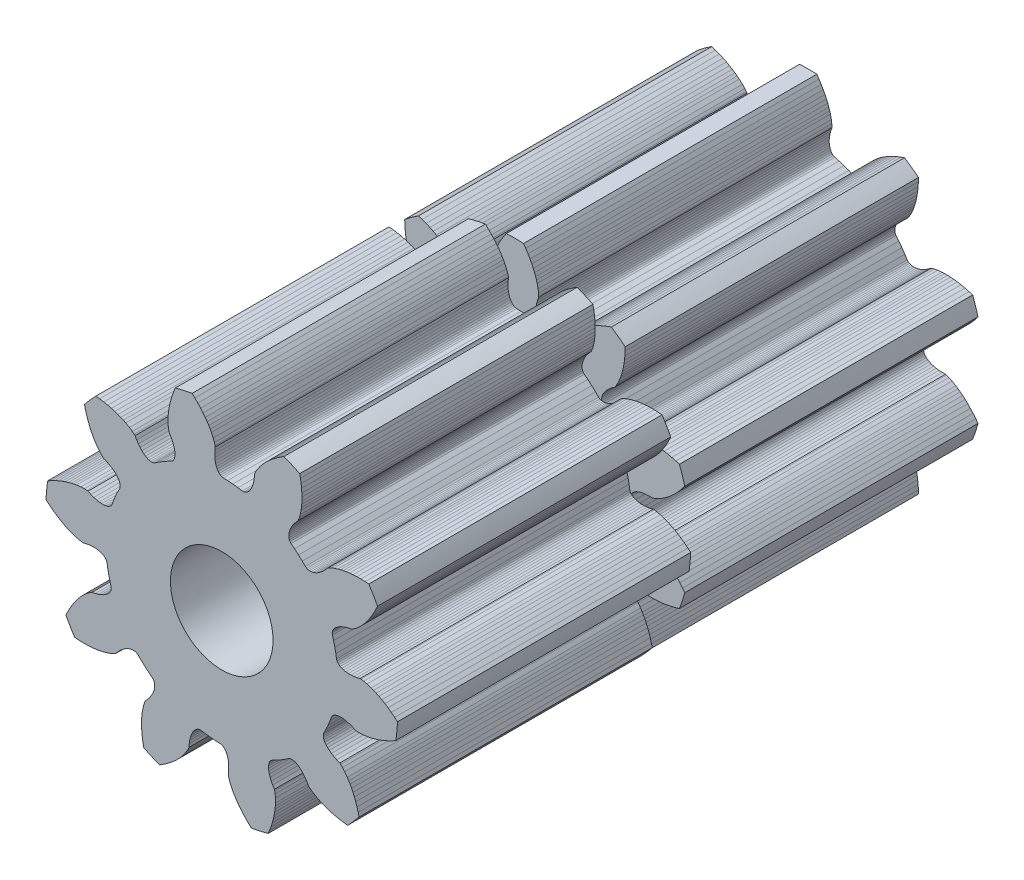
SolidWorks part; units mm, degrees
ref_plane "Front Plane" through (0, 0, 0) normal (0, 0, 1) x (1, 0, 0)
ref_plane "Top Plane" through (0, 0, 0) normal (0, 1, 0) x (1, 0, 0)
ref_plane "Right Plane" through (0, 0, 0) normal (1, 0, 0) x (0, 0, -1)
sketch "Sketch1" plane through (0, 0, 0) normal (0, 0, 1) x (1, 0, 0)
  line L0 (11.2428, -4.5485) -> (11.2517, -4.4039)
  line L1 (11.2517, -4.4039) -> (11.266, -4.2669)
  line L2 (11.266, -4.2669) -> (11.2847, -4.1393)
  line L3 (11.2847, -4.1393) -> (11.3071, -4.0209)
  line L4 (11.3071, -4.0209) -> (11.3325, -3.912)
  line L5 (11.3325, -3.912) -> (11.3608, -3.8103)
  line L6 (11.3608, -3.8103) -> (11.3897, -3.7211)
  line L7 (11.3897, -3.7211) -> (11.4208, -3.6371)
  line L8 (11.4208, -3.6371) -> (11.4807, -3.5016)
  line L9 (11.4807, -3.5016) -> (11.5377, -3.3971)
  line L10 (11.5377, -3.3971) -> (11.5845, -3.3262)
  line L11 (11.5845, -3.3262) -> (11.6076, -3.2964)
  line L12 (11.6076, -3.2964) -> (11.7007, -3.2317)
  line L13 (11.7007, -3.2317) -> (11.7827, -3.1653)
  line L14 (11.7827, -3.1653) -> (11.8533, -3.098)
  line L15 (11.8533, -3.098) -> (11.9128, -3.0308)
  line L16 (11.9128, -3.0308) -> (11.9612, -2.9643)
  line L17 (11.9612, -2.9643) -> (11.9989, -2.8995)
  line L18 (11.9989, -2.8995) -> (12.0259, -2.837)
  line L19 (12.0259, -2.837) -> (12.0426, -2.7776)
  line L20 (12.0426, -2.7776) -> (12.0493, -2.7222)
  line L21 (12.0493, -2.7222) -> (12.0463, -2.6714)
  line L22 (12.0463, -2.6714) -> (12.0342, -2.6259)
  line L23 (12.0342, -2.6259) -> (12.0067, -2.5776)
  line L24 (12.0067, -2.5776) -> (11.9109, -2.4617)
  line L25 (11.9109, -2.4617) -> (11.8044, -2.3217)
  line L26 (11.8044, -2.3217) -> (11.7041, -2.1772)
  line L27 (11.7041, -2.1772) -> (11.6236, -2.0503)
  line L28 (11.6236, -2.0503) -> (11.5861, -2.0092)
  line L29 (11.5861, -2.0092) -> (11.5466, -1.9836)
  line L30 (11.5466, -1.9836) -> (11.4992, -1.9651)
  line L31 (11.4992, -1.9651) -> (11.4444, -1.9543)
  line L32 (11.4444, -1.9543) -> (11.3828, -1.9518)
  line L33 (11.3828, -1.9518) -> (11.315, -1.9582)
  line L34 (11.315, -1.9582) -> (11.2417, -1.974)
  line L35 (11.2417, -1.974) -> (11.1635, -1.9995)
  line L36 (11.1635, -1.9995) -> (11.0812, -2.0353)
  line L37 (11.0812, -2.0353) -> (10.9954, -2.0817)
  line L38 (10.9954, -2.0817) -> (10.907, -2.1391)
  line L39 (10.907, -2.1391) -> (10.8166, -2.2077)
  line L40 (10.8166, -2.2077) -> (10.7811, -2.2204)
  line L41 (10.7811, -2.2204) -> (10.6992, -2.243)
  line L42 (10.6992, -2.243) -> (10.5823, -2.2649)
  line L43 (10.5823, -2.2649) -> (10.4348, -2.2801)
  line L44 (10.4348, -2.2801) -> (10.3453, -2.2837)
  line L45 (10.3453, -2.2837) -> (10.2516, -2.2836)
  line L46 (10.2516, -2.2836) -> (10.1461, -2.2791)
  line L47 (10.1461, -2.2791) -> (10.0348, -2.2696)
  line L48 (10.0348, -2.2696) -> (9.9151, -2.2543)
  line L49 (9.9151, -2.2543) -> (9.7881, -2.2327)
  line L50 (9.7881, -2.2327) -> (9.6533, -2.2039)
  line L51 (9.6533, -2.2039) -> (9.5131, -2.1677)
  line L52 (9.5131, -2.1677) -> (9.3912, -2.1311)
  line L53 (9.2098, -1.5726) -> (9.2868, -1.4714)
  line L54 (9.2868, -1.4714) -> (9.379, -1.3597)
  line L55 (9.379, -1.3597) -> (9.4711, -1.2572)
  line L56 (9.4711, -1.2572) -> (9.5612, -1.165)
  line L57 (9.5612, -1.165) -> (9.649, -1.0823)
  line L58 (9.649, -1.0823) -> (9.7335, -1.0092)
  line L59 (9.7335, -1.0092) -> (9.8162, -0.9435)
  line L60 (9.8162, -0.9435) -> (9.8919, -0.8883)
  line L61 (9.8919, -0.8883) -> (9.9665, -0.8387)
  line L62 (9.9665, -0.8387) -> (10.0947, -0.7642)
  line L63 (10.0947, -0.7642) -> (10.2021, -0.7133)
  line L64 (10.2021, -0.7133) -> (10.2817, -0.6834)
  line L65 (10.2817, -0.6834) -> (10.3179, -0.6728)
  line L66 (10.3179, -0.6728) -> (10.4313, -0.6752)
  line L67 (10.4313, -0.6752) -> (10.5366, -0.6696)
  line L68 (10.5366, -0.6696) -> (10.6333, -0.6568)
  line L69 (10.6333, -0.6568) -> (10.7209, -0.6373)
  line L70 (10.7209, -0.6373) -> (10.7992, -0.612)
  line L71 (10.7992, -0.612) -> (10.8678, -0.5817)
  line L72 (10.8678, -0.5817) -> (10.9263, -0.547)
  line L73 (10.9263, -0.547) -> (10.9747, -0.5088)
  line L74 (10.9747, -0.5088) -> (11.0127, -0.4679)
  line L75 (11.0127, -0.4679) -> (11.0402, -0.4251)
  line L76 (11.0402, -0.4251) -> (11.0571, -0.3811)
  line L77 (11.0571, -0.3811) -> (11.0633, -0.3259)
  line L78 (11.0633, -0.3259) -> (11.0539, -0.1759)
  line L79 (11.0539, -0.1759) -> (11.05, 0)
  line L80 (11.05, 0) -> (11.0539, 0.1759)
  line L81 (11.0539, 0.1759) -> (11.0633, 0.3259)
  line L82 (11.0633, 0.3259) -> (11.0571, 0.3812)
  line L83 (11.0571, 0.3812) -> (11.0402, 0.4251)
  line L84 (11.0402, 0.4251) -> (11.0127, 0.468)
  line L85 (11.0127, 0.468) -> (10.9747, 0.5089)
  line L86 (10.9747, 0.5089) -> (10.9263, 0.5471)
  line L87 (10.9263, 0.5471) -> (10.8678, 0.5817)
  line L88 (10.8678, 0.5817) -> (10.7992, 0.6121)
  line L89 (10.7992, 0.6121) -> (10.7209, 0.6374)
  line L90 (10.7209, 0.6374) -> (10.6333, 0.6568)
  line L91 (10.6333, 0.6568) -> (10.5366, 0.6697)
  line L92 (10.5366, 0.6697) -> (10.4313, 0.6753)
  line L93 (10.4313, 0.6753) -> (10.3179, 0.6729)
  line L94 (10.3179, 0.6729) -> (10.2817, 0.6834)
  line L95 (10.2817, 0.6834) -> (10.2021, 0.7133)
  line L96 (10.2021, 0.7133) -> (10.0947, 0.7643)
  line L97 (10.0947, 0.7643) -> (9.9665, 0.8387)
  line L98 (9.9665, 0.8387) -> (9.8919, 0.8884)
  line L99 (9.8919, 0.8884) -> (9.8162, 0.9436)
  line L100 (9.8162, 0.9436) -> (9.7335, 1.0093)
  line L101 (9.7335, 1.0093) -> (9.649, 1.0824)
  line L102 (9.649, 1.0824) -> (9.5612, 1.165)
  line L103 (9.5612, 1.165) -> (9.4711, 1.2572)
  line L104 (9.4711, 1.2572) -> (9.379, 1.3597)
  line L105 (9.379, 1.3597) -> (9.2868, 1.4714)
  line L106 (9.2868, 1.4714) -> (9.2098, 1.5727)
  line L107 (9.3912, 2.1311) -> (9.5131, 2.1677)
  line L108 (9.5131, 2.1677) -> (9.6533, 2.2039)
  line L109 (9.6533, 2.2039) -> (9.788, 2.2327)
  line L110 (9.788, 2.2327) -> (9.9151, 2.2544)
  line L111 (9.9151, 2.2544) -> (10.0347, 2.2696)
  line L112 (10.0347, 2.2696) -> (10.1461, 2.2791)
  line L113 (10.1461, 2.2791) -> (10.2516, 2.2836)
  line L114 (10.2516, 2.2836) -> (10.3453, 2.2837)
  line L115 (10.3453, 2.2837) -> (10.4348, 2.2801)
  line L116 (10.4348, 2.2801) -> (10.5823, 2.265)
  line L117 (10.5823, 2.265) -> (10.6992, 2.2431)
  line L118 (10.6992, 2.2431) -> (10.7811, 2.2205)
  line L119 (10.7811, 2.2205) -> (10.8166, 2.2078)
  line L120 (10.8166, 2.2078) -> (10.9069, 2.1391)
  line L121 (10.9069, 2.1391) -> (10.9954, 2.0818)
  line L122 (10.9954, 2.0818) -> (11.0812, 2.0353)
  line L123 (11.0812, 2.0353) -> (11.1635, 1.9995)
  line L124 (11.1635, 1.9995) -> (11.2417, 1.974)
  line L125 (11.2417, 1.974) -> (11.315, 1.9583)
  line L126 (11.315, 1.9583) -> (11.3828, 1.9519)
  line L127 (11.3828, 1.9519) -> (11.4444, 1.9543)
  line L128 (11.4444, 1.9543) -> (11.4991, 1.9651)
  line L129 (11.4991, 1.9651) -> (11.5465, 1.9836)
  line L130 (11.5465, 1.9836) -> (11.586, 2.0092)
  line L131 (11.586, 2.0092) -> (11.6235, 2.0503)
  line L132 (11.6235, 2.0503) -> (11.7041, 2.1772)
  line L133 (11.7041, 2.1772) -> (11.8043, 2.3218)
  line L134 (11.8043, 2.3218) -> (11.9109, 2.4618)
  line L135 (11.9109, 2.4618) -> (12.0067, 2.5776)
  line L136 (12.0067, 2.5776) -> (12.0341, 2.626)
  line L137 (12.0341, 2.626) -> (12.0463, 2.6715)
  line L138 (12.0463, 2.6715) -> (12.0492, 2.7223)
  line L139 (12.0492, 2.7223) -> (12.0426, 2.7777)
  line L140 (12.0426, 2.7777) -> (12.0259, 2.837)
  line L141 (12.0259, 2.837) -> (11.9988, 2.8995)
  line L142 (11.9988, 2.8995) -> (11.9612, 2.9643)
  line L143 (11.9612, 2.9643) -> (11.9128, 3.0308)
  line L144 (11.9128, 3.0308) -> (11.8533, 3.0981)
  line L145 (11.8533, 3.0981) -> (11.7826, 3.1653)
  line L146 (11.7826, 3.1653) -> (11.7007, 3.2317)
  line L147 (11.7007, 3.2317) -> (11.6075, 3.2964)
  line L148 (11.6075, 3.2964) -> (11.5845, 3.3262)
  line L149 (11.5845, 3.3262) -> (11.5377, 3.3972)
  line L150 (11.5377, 3.3972) -> (11.4807, 3.5016)
  line L151 (11.4807, 3.5016) -> (11.4208, 3.6372)
  line L152 (11.4208, 3.6372) -> (11.3896, 3.7212)
  line L153 (11.3896, 3.7212) -> (11.3608, 3.8103)
  line L154 (11.3608, 3.8103) -> (11.3325, 3.9121)
  line L155 (11.3325, 3.9121) -> (11.3071, 4.0209)
  line L156 (11.3071, 4.0209) -> (11.2846, 4.1394)
  line L157 (11.2846, 4.1394) -> (11.2659, 4.2669)
  line L158 (11.2659, 4.2669) -> (11.2517, 4.404)
  line L159 (11.2517, 4.404) -> (11.2428, 4.5485)
  line L160 (11.2428, 4.5485) -> (11.2399, 4.6757)
  line L161 (11.715, 5.0209) -> (11.8351, 4.9789)
  line L162 (11.8351, 4.9789) -> (11.9698, 4.9257)
  line L163 (11.9698, 4.9257) -> (12.0958, 4.8698)
  line L164 (12.0958, 4.8698) -> (12.2113, 4.8127)
  line L165 (12.2113, 4.8127) -> (12.3171, 4.7547)
  line L166 (12.3171, 4.7547) -> (12.4127, 4.6969)
  line L167 (12.4127, 4.6969) -> (12.5007, 4.6385)
  line L168 (12.5007, 4.6385) -> (12.5766, 4.5836)
  line L169 (12.5766, 4.5836) -> (12.6469, 4.528)
  line L170 (12.6469, 4.528) -> (12.7573, 4.4291)
  line L171 (12.7573, 4.4291) -> (12.839, 4.3427)
  line L172 (12.839, 4.3427) -> (12.892, 4.2762)
  line L173 (12.892, 4.2762) -> (12.9132, 4.2451)
  line L174 (12.9132, 4.2451) -> (12.946, 4.1364)
  line L175 (12.946, 4.1364) -> (12.9838, 4.038)
  line L176 (12.9838, 4.038) -> (13.0259, 3.9501)
  line L177 (13.0259, 3.9501) -> (13.0715, 3.8727)
  line L178 (13.0715, 3.8727) -> (13.1197, 3.8061)
  line L179 (13.1197, 3.8061) -> (13.1698, 3.7503)
  line L180 (13.1698, 3.7503) -> (13.2209, 3.7053)
  line L181 (13.2209, 3.7053) -> (13.2721, 3.671)
  line L182 (13.2721, 3.671) -> (13.3228, 3.6476)
  line L183 (13.3228, 3.6476) -> (13.372, 3.6347)
  line L184 (13.372, 3.6347) -> (13.419, 3.6322)
  line L185 (13.419, 3.6322) -> (13.4735, 3.6434)
  line L186 (13.4735, 3.6434) -> (13.6133, 3.6987)
  line L187 (13.6133, 3.6987) -> (13.7794, 3.7567)
  line L188 (13.7794, 3.7567) -> (13.9478, 3.8074)
  line L189 (13.9478, 3.8074) -> (14.0934, 3.8448)
  line L190 (14.0934, 3.8448) -> (14.1441, 3.8678)
  line L191 (14.1441, 3.8678) -> (14.1806, 3.8974)
  line L192 (14.1806, 3.8974) -> (14.2129, 3.9368)
  line L193 (14.2129, 3.9368) -> (14.2401, 3.9855)
  line L194 (14.2401, 3.9855) -> (14.2614, 4.0434)
  line L195 (14.2614, 4.0434) -> (14.2763, 4.1098)
  line L196 (14.2763, 4.1098) -> (14.284, 4.1844)
  line L197 (14.284, 4.1844) -> (14.2838, 4.2666)
  line L198 (14.2838, 4.2666) -> (14.2752, 4.356)
  line L199 (14.2752, 4.356) -> (14.2576, 4.4519)
  line L200 (14.2576, 4.4519) -> (14.2304, 4.5538)
  line L201 (14.2304, 4.5538) -> (14.193, 4.6609)
  line L202 (14.193, 4.6609) -> (14.1919, 4.6986)
  line L203 (14.1919, 4.6986) -> (14.1957, 4.7835)
  line L204 (14.1957, 4.7835) -> (14.211, 4.9014)
  line L205 (14.211, 4.9014) -> (14.2422, 5.0463)
  line L206 (14.2422, 5.0463) -> (14.2664, 5.1326)
  line L207 (14.2664, 5.1326) -> (14.2955, 5.2217)
  line L208 (14.2955, 5.2217) -> (14.3324, 5.3207)
  line L209 (14.3324, 5.3207) -> (14.3758, 5.4236)
  line L210 (14.3758, 5.4236) -> (14.4273, 5.5327)
  line L211 (14.4273, 5.5327) -> (14.4871, 5.6468)
  line L212 (14.4871, 5.6468) -> (14.5562, 5.7661)
  line L213 (14.5562, 5.7661) -> (14.6339, 5.8883)
  line L214 (14.6339, 5.8883) -> (14.7064, 5.9928)
  line L215 (15.2936, 5.9928) -> (15.3661, 5.8883)
  line L216 (15.3661, 5.8883) -> (15.4438, 5.7661)
  line L217 (15.4438, 5.7661) -> (15.5128, 5.6468)
  line L218 (15.5128, 5.6468) -> (15.5727, 5.5327)
  line L219 (15.5727, 5.5327) -> (15.6242, 5.4236)
  line L220 (15.6242, 5.4236) -> (15.6676, 5.3207)
  line L221 (15.6676, 5.3207) -> (15.7045, 5.2217)
  line L222 (15.7045, 5.2217) -> (15.7336, 5.1326)
  line L223 (15.7336, 5.1326) -> (15.7578, 5.0464)
  line L224 (15.7578, 5.0464) -> (15.7889, 4.9014)
  line L225 (15.7889, 4.9014) -> (15.8042, 4.7835)
  line L226 (15.8042, 4.7835) -> (15.8081, 4.6986)
  line L227 (15.8081, 4.6986) -> (15.8069, 4.6609)
  line L228 (15.8069, 4.6609) -> (15.7696, 4.5538)
  line L229 (15.7696, 4.5538) -> (15.7424, 4.4519)
  line L230 (15.7424, 4.4519) -> (15.7247, 4.356)
  line L231 (15.7247, 4.356) -> (15.7161, 4.2666)
  line L232 (15.7161, 4.2666) -> (15.716, 4.1844)
  line L233 (15.716, 4.1844) -> (15.7237, 4.1098)
  line L234 (15.7237, 4.1098) -> (15.7385, 4.0434)
  line L235 (15.7385, 4.0434) -> (15.7599, 3.9855)
  line L236 (15.7599, 3.9855) -> (15.7871, 3.9368)
  line L237 (15.7871, 3.9368) -> (15.8193, 3.8974)
  line L238 (15.8193, 3.8974) -> (15.8559, 3.8678)
  line L239 (15.8559, 3.8678) -> (15.9065, 3.8448)
  line L240 (15.9065, 3.8448) -> (16.0521, 3.8074)
  line L241 (16.0521, 3.8074) -> (16.2206, 3.7567)
  line L242 (16.2206, 3.7567) -> (16.3867, 3.6987)
  line L243 (16.3867, 3.6987) -> (16.5264, 3.6434)
  line L244 (16.5264, 3.6434) -> (16.5809, 3.6322)
  line L245 (16.5809, 3.6322) -> (16.6279, 3.6347)
  line L246 (16.6279, 3.6347) -> (16.6772, 3.6476)
  line L247 (16.6772, 3.6476) -> (16.7278, 3.6711)
  line L248 (16.7278, 3.6711) -> (16.7791, 3.7053)
  line L249 (16.7791, 3.7053) -> (16.8301, 3.7503)
  line L250 (16.8301, 3.7503) -> (16.8802, 3.8061)
  line L251 (16.8802, 3.8061) -> (16.9284, 3.8727)
  line L252 (16.9284, 3.8727) -> (16.974, 3.9501)
  line L253 (16.974, 3.9501) -> (17.0161, 4.038)
  line L254 (17.0161, 4.038) -> (17.054, 4.1365)
  line L255 (17.054, 4.1365) -> (17.0867, 4.2451)
  line L256 (17.0867, 4.2451) -> (17.108, 4.2762)
  line L257 (17.108, 4.2762) -> (17.161, 4.3427)
  line L258 (17.161, 4.3427) -> (17.2427, 4.4291)
  line L259 (17.2427, 4.4291) -> (17.3531, 4.528)
  line L260 (17.3531, 4.528) -> (17.4233, 4.5836)
  line L261 (17.4233, 4.5836) -> (17.4992, 4.6385)
  line L262 (17.4992, 4.6385) -> (17.5873, 4.6969)
  line L263 (17.5873, 4.6969) -> (17.6829, 4.7547)
  line L264 (17.6829, 4.7547) -> (17.7886, 4.8127)
  line L265 (17.7886, 4.8127) -> (17.9042, 4.8699)
  line L266 (17.9042, 4.8699) -> (18.0301, 4.9258)
  line L267 (18.0301, 4.9258) -> (18.1648, 4.9789)
  line L268 (18.1648, 4.9789) -> (18.2849, 5.0209)
  line L269 (18.76, 4.6758) -> (18.7572, 4.5486)
  line L270 (18.7572, 4.5486) -> (18.7483, 4.404)
  line L271 (18.7483, 4.404) -> (18.734, 4.2669)
  line L272 (18.734, 4.2669) -> (18.7153, 4.1394)
  line L273 (18.7153, 4.1394) -> (18.6928, 4.0209)
  line L274 (18.6928, 4.0209) -> (18.6675, 3.9121)
  line L275 (18.6675, 3.9121) -> (18.6392, 3.8103)
  line L276 (18.6392, 3.8103) -> (18.6103, 3.7212)
  line L277 (18.6103, 3.7212) -> (18.5792, 3.6372)
  line L278 (18.5792, 3.6372) -> (18.5192, 3.5016)
  line L279 (18.5192, 3.5016) -> (18.4623, 3.3972)
  line L280 (18.4623, 3.3972) -> (18.4155, 3.3263)
  line L281 (18.4155, 3.3263) -> (18.3924, 3.2965)
  line L282 (18.3924, 3.2965) -> (18.2992, 3.2317)
  line L283 (18.2992, 3.2317) -> (18.2173, 3.1653)
  line L284 (18.2173, 3.1653) -> (18.1467, 3.0981)
  line L285 (18.1467, 3.0981) -> (18.0872, 3.0308)
  line L286 (18.0872, 3.0308) -> (18.0387, 2.9644)
  line L287 (18.0387, 2.9644) -> (18.0011, 2.8995)
  line L288 (18.0011, 2.8995) -> (17.9741, 2.837)
  line L289 (17.9741, 2.837) -> (17.9574, 2.7777)
  line L290 (17.9574, 2.7777) -> (17.9507, 2.7223)
  line L291 (17.9507, 2.7223) -> (17.9537, 2.6715)
  line L292 (17.9537, 2.6715) -> (17.9658, 2.626)
  line L293 (17.9658, 2.626) -> (17.9933, 2.5777)
  line L294 (17.9933, 2.5777) -> (18.0891, 2.4618)
  line L295 (18.0891, 2.4618) -> (18.1956, 2.3218)
  line L296 (18.1956, 2.3218) -> (18.2959, 2.1772)
  line L297 (18.2959, 2.1772) -> (18.3764, 2.0503)
  line L298 (18.3764, 2.0503) -> (18.4139, 2.0093)
  line L299 (18.4139, 2.0093) -> (18.4534, 1.9836)
  line L300 (18.4534, 1.9836) -> (18.5008, 1.9651)
  line L301 (18.5008, 1.9651) -> (18.5556, 1.9544)
  line L302 (18.5556, 1.9544) -> (18.6172, 1.9519)
  line L303 (18.6172, 1.9519) -> (18.6849, 1.9583)
  line L304 (18.6849, 1.9583) -> (18.7583, 1.974)
  line L305 (18.7583, 1.974) -> (18.8364, 1.9996)
  line L306 (18.8364, 1.9996) -> (18.9188, 2.0354)
  line L307 (18.9188, 2.0354) -> (19.0046, 2.0818)
  line L308 (19.0046, 2.0818) -> (19.093, 2.1392)
  line L309 (19.093, 2.1392) -> (19.1834, 2.2078)
  line L310 (19.1834, 2.2078) -> (19.2188, 2.2205)
  line L311 (19.2188, 2.2205) -> (19.3008, 2.2431)
  line L312 (19.3008, 2.2431) -> (19.4177, 2.265)
  line L313 (19.4177, 2.265) -> (19.5651, 2.2801)
  line L314 (19.5651, 2.2801) -> (19.6547, 2.2838)
  line L315 (19.6547, 2.2838) -> (19.7484, 2.2837)
  line L316 (19.7484, 2.2837) -> (19.8539, 2.2791)
  line L317 (19.8539, 2.2791) -> (19.9652, 2.2696)
  line L318 (19.9652, 2.2696) -> (20.0848, 2.2544)
  line L319 (20.0848, 2.2544) -> (20.2119, 2.2328)
  line L320 (20.2119, 2.2328) -> (20.3467, 2.204)
  line L321 (20.3467, 2.204) -> (20.4869, 2.1678)
  line L322 (20.4869, 2.1678) -> (20.6088, 2.1312)
  line L323 (20.7902, 1.5727) -> (20.7132, 1.4714)
  line L324 (20.7132, 1.4714) -> (20.621, 1.3598)
  line L325 (20.621, 1.3598) -> (20.5289, 1.2572)
  line L326 (20.5289, 1.2572) -> (20.4388, 1.165)
  line L327 (20.4388, 1.165) -> (20.351, 1.0824)
  line L328 (20.351, 1.0824) -> (20.2665, 1.0093)
  line L329 (20.2665, 1.0093) -> (20.1838, 0.9436)
  line L330 (20.1838, 0.9436) -> (20.108, 0.8884)
  line L331 (20.108, 0.8884) -> (20.0335, 0.8388)
  line L332 (20.0335, 0.8388) -> (19.9053, 0.7643)
  line L333 (19.9053, 0.7643) -> (19.7979, 0.7133)
  line L334 (19.7979, 0.7133) -> (19.7183, 0.6834)
  line L335 (19.7183, 0.6834) -> (19.6821, 0.6729)
  line L336 (19.6821, 0.6729) -> (19.5687, 0.6753)
  line L337 (19.5687, 0.6753) -> (19.4634, 0.6697)
  line L338 (19.4634, 0.6697) -> (19.3667, 0.6568)
  line L339 (19.3667, 0.6568) -> (19.279, 0.6374)
  line L340 (19.279, 0.6374) -> (19.2008, 0.6121)
  line L341 (19.2008, 0.6121) -> (19.1322, 0.5818)
  line L342 (19.1322, 0.5818) -> (19.0736, 0.5471)
  line L343 (19.0736, 0.5471) -> (19.0253, 0.5089)
  line L344 (19.0253, 0.5089) -> (18.9873, 0.468)
  line L345 (18.9873, 0.468) -> (18.9598, 0.4252)
  line L346 (18.9598, 0.4252) -> (18.9429, 0.3812)
  line L347 (18.9429, 0.3812) -> (18.9367, 0.3259)
  line L348 (18.9367, 0.3259) -> (18.9461, 0.1759)
  line L349 (18.9461, 0.1759) -> (18.95, 0)
  line L350 (18.95, 0) -> (18.9461, -0.1758)
  line L351 (18.9461, -0.1758) -> (18.9367, -0.3259)
  line L352 (18.9367, -0.3259) -> (18.9429, -0.3811)
  line L353 (18.9429, -0.3811) -> (18.9598, -0.4251)
  line L354 (18.9598, -0.4251) -> (18.9873, -0.4679)
  line L355 (18.9873, -0.4679) -> (19.0253, -0.5088)
  line L356 (19.0253, -0.5088) -> (19.0736, -0.547)
  line L357 (19.0736, -0.547) -> (19.1322, -0.5817)
  line L358 (19.1322, -0.5817) -> (19.2008, -0.612)
  line L359 (19.2008, -0.612) -> (19.279, -0.6373)
  line L360 (19.279, -0.6373) -> (19.3667, -0.6567)
  line L361 (19.3667, -0.6567) -> (19.4634, -0.6696)
  line L362 (19.4634, -0.6696) -> (19.5687, -0.6752)
  line L363 (19.5687, -0.6752) -> (19.6821, -0.6728)
  line L364 (19.6821, -0.6728) -> (19.7183, -0.6834)
  line L365 (19.7183, -0.6834) -> (19.7979, -0.7132)
  line L366 (19.7979, -0.7132) -> (19.9053, -0.7642)
  line L367 (19.9053, -0.7642) -> (20.0335, -0.8387)
  line L368 (20.0335, -0.8387) -> (20.108, -0.8883)
  line L369 (20.108, -0.8883) -> (20.1838, -0.9435)
  line L370 (20.1838, -0.9435) -> (20.2665, -1.0092)
  line L371 (20.2665, -1.0092) -> (20.351, -1.0823)
  line L372 (20.351, -1.0823) -> (20.4388, -1.1649)
  line L373 (20.4388, -1.1649) -> (20.5289, -1.2571)
  line L374 (20.5289, -1.2571) -> (20.621, -1.3597)
  line L375 (20.621, -1.3597) -> (20.7132, -1.4714)
  line L376 (20.7132, -1.4714) -> (20.7902, -1.5726)
  line L377 (20.6088, -2.131) -> (20.4869, -2.1677)
  line L378 (20.4869, -2.1677) -> (20.3467, -2.2039)
  line L379 (20.3467, -2.2039) -> (20.2119, -2.2327)
  line L380 (20.2119, -2.2327) -> (20.0849, -2.2543)
  line L381 (20.0849, -2.2543) -> (19.9652, -2.2695)
  line L382 (19.9652, -2.2695) -> (19.8539, -2.279)
  line L383 (19.8539, -2.279) -> (19.7484, -2.2836)
  line L384 (19.7484, -2.2836) -> (19.6547, -2.2837)
  line L385 (19.6547, -2.2837) -> (19.5652, -2.28)
  line L386 (19.5652, -2.28) -> (19.4177, -2.2649)
  line L387 (19.4177, -2.2649) -> (19.3008, -2.243)
  line L388 (19.3008, -2.243) -> (19.2189, -2.2204)
  line L389 (19.2189, -2.2204) -> (19.1834, -2.2077)
  line L390 (19.1834, -2.2077) -> (19.093, -2.1391)
  line L391 (19.093, -2.1391) -> (19.0046, -2.0817)
  line L392 (19.0046, -2.0817) -> (18.9188, -2.0353)
  line L393 (18.9188, -2.0353) -> (18.8365, -1.9995)
  line L394 (18.8365, -1.9995) -> (18.7583, -1.9739)
  line L395 (18.7583, -1.9739) -> (18.685, -1.9582)
  line L396 (18.685, -1.9582) -> (18.6172, -1.9518)
  line L397 (18.6172, -1.9518) -> (18.5556, -1.9543)
  line L398 (18.5556, -1.9543) -> (18.5008, -1.965)
  line L399 (18.5008, -1.965) -> (18.4534, -1.9835)
  line L400 (18.4534, -1.9835) -> (18.4139, -2.0092)
  line L401 (18.4139, -2.0092) -> (18.3764, -2.0502)
  line L402 (18.3764, -2.0502) -> (18.2959, -2.1771)
  line L403 (18.2959, -2.1771) -> (18.1956, -2.3217)
  line L404 (18.1956, -2.3217) -> (18.0891, -2.4617)
  line L405 (18.0891, -2.4617) -> (17.9933, -2.5776)
  line L406 (17.9933, -2.5776) -> (17.9658, -2.6259)
  line L407 (17.9658, -2.6259) -> (17.9537, -2.6714)
  line L408 (17.9537, -2.6714) -> (17.9507, -2.7222)
  line L409 (17.9507, -2.7222) -> (17.9574, -2.7776)
  line L410 (17.9574, -2.7776) -> (17.9741, -2.8369)
  line L411 (17.9741, -2.8369) -> (18.0011, -2.8994)
  line L412 (18.0011, -2.8994) -> (18.0387, -2.9643)
  line L413 (18.0387, -2.9643) -> (18.0872, -3.0307)
  line L414 (18.0872, -3.0307) -> (18.1467, -3.098)
  line L415 (18.1467, -3.098) -> (18.2173, -3.1652)
  line L416 (18.2173, -3.1652) -> (18.2992, -3.2316)
  line L417 (18.2992, -3.2316) -> (18.3924, -3.2964)
  line L418 (18.3924, -3.2964) -> (18.4155, -3.3262)
  line L419 (18.4155, -3.3262) -> (18.4623, -3.3971)
  line L420 (18.4623, -3.3971) -> (18.5193, -3.5015)
  line L421 (18.5193, -3.5015) -> (18.5792, -3.6371)
  line L422 (18.5792, -3.6371) -> (18.6103, -3.7211)
  line L423 (18.6103, -3.7211) -> (18.6392, -3.8102)
  line L424 (18.6392, -3.8102) -> (18.6675, -3.912)
  line L425 (18.6675, -3.912) -> (18.6929, -4.0208)
  line L426 (18.6929, -4.0208) -> (18.7153, -4.1393)
  line L427 (18.7153, -4.1393) -> (18.734, -4.2668)
  line L428 (18.734, -4.2668) -> (18.7483, -4.4039)
  line L429 (18.7483, -4.4039) -> (18.7572, -4.5484)
  line L430 (18.7572, -4.5484) -> (18.76, -4.6757)
  line L431 (18.285, -5.0208) -> (18.1648, -4.9788)
  line L432 (18.1648, -4.9788) -> (18.0301, -4.9257)
  line L433 (18.0301, -4.9257) -> (17.9042, -4.8698)
  line L434 (17.9042, -4.8698) -> (17.7886, -4.8126)
  line L435 (17.7886, -4.8126) -> (17.6829, -4.7546)
  line L436 (17.6829, -4.7546) -> (17.5873, -4.6968)
  line L437 (17.5873, -4.6968) -> (17.4992, -4.6385)
  line L438 (17.4992, -4.6385) -> (17.4234, -4.5835)
  line L439 (17.4234, -4.5835) -> (17.3531, -4.5279)
  line L440 (17.3531, -4.5279) -> (17.2427, -4.429)
  line L441 (17.2427, -4.429) -> (17.161, -4.3426)
  line L442 (17.161, -4.3426) -> (17.108, -4.2761)
  line L443 (17.108, -4.2761) -> (17.0868, -4.245)
  line L444 (17.0868, -4.245) -> (17.054, -4.1364)
  line L445 (17.054, -4.1364) -> (17.0161, -4.038)
  line L446 (17.0161, -4.038) -> (16.974, -3.95)
  line L447 (16.974, -3.95) -> (16.9284, -3.8726)
  line L448 (16.9284, -3.8726) -> (16.8802, -3.806)
  line L449 (16.8802, -3.806) -> (16.8302, -3.7502)
  line L450 (16.8302, -3.7502) -> (16.7791, -3.7052)
  line L451 (16.7791, -3.7052) -> (16.7278, -3.671)
  line L452 (16.7278, -3.671) -> (16.6772, -3.6475)
  line L453 (16.6772, -3.6475) -> (16.6279, -3.6346)
  line L454 (16.6279, -3.6346) -> (16.5809, -3.6321)
  line L455 (16.5809, -3.6321) -> (16.5265, -3.6433)
  line L456 (16.5265, -3.6433) -> (16.3867, -3.6986)
  line L457 (16.3867, -3.6986) -> (16.2206, -3.7567)
  line L458 (16.2206, -3.7567) -> (16.0521, -3.8073)
  line L459 (16.0521, -3.8073) -> (15.9066, -3.8447)
  line L460 (15.9066, -3.8447) -> (15.8559, -3.8677)
  line L461 (15.8559, -3.8677) -> (15.8193, -3.8973)
  line L462 (15.8193, -3.8973) -> (15.7871, -3.9367)
  line L463 (15.7871, -3.9367) -> (15.7599, -3.9855)
  line L464 (15.7599, -3.9855) -> (15.7385, -4.0433)
  line L465 (15.7385, -4.0433) -> (15.7237, -4.1097)
  line L466 (15.7237, -4.1097) -> (15.716, -4.1843)
  line L467 (15.716, -4.1843) -> (15.7161, -4.2665)
  line L468 (15.7161, -4.2665) -> (15.7247, -4.3559)
  line L469 (15.7247, -4.3559) -> (15.7424, -4.4518)
  line L470 (15.7424, -4.4518) -> (15.7696, -4.5537)
  line L471 (15.7696, -4.5537) -> (15.8069, -4.6609)
  line L472 (15.8069, -4.6609) -> (15.8081, -4.6985)
  line L473 (15.8081, -4.6985) -> (15.8042, -4.7834)
  line L474 (15.8042, -4.7834) -> (15.789, -4.9014)
  line L475 (15.789, -4.9014) -> (15.7578, -5.0463)
  line L476 (15.7578, -5.0463) -> (15.7336, -5.1325)
  line L477 (15.7336, -5.1325) -> (15.7045, -5.2216)
  line L478 (15.7045, -5.2216) -> (15.6676, -5.3206)
  line L479 (15.6676, -5.3206) -> (15.6242, -5.4235)
  line L480 (15.6242, -5.4235) -> (15.5727, -5.5326)
  line L481 (15.5727, -5.5326) -> (15.5129, -5.6468)
  line L482 (15.5129, -5.6468) -> (15.4438, -5.766)
  line L483 (15.4438, -5.766) -> (15.3661, -5.8882)
  line L484 (15.3661, -5.8882) -> (15.2936, -5.9928)
  line L485 (14.7064, -5.9928) -> (14.6339, -5.8882)
  line L486 (14.6339, -5.8882) -> (14.5561, -5.766)
  line L487 (14.5561, -5.766) -> (14.4871, -5.6468)
  line L488 (14.4871, -5.6468) -> (14.4272, -5.5326)
  line L489 (14.4272, -5.5326) -> (14.3758, -5.4235)
  line L490 (14.3758, -5.4235) -> (14.3324, -5.3206)
  line L491 (14.3324, -5.3206) -> (14.2954, -5.2216)
  line L492 (14.2954, -5.2216) -> (14.2664, -5.1325)
  line L493 (14.2664, -5.1325) -> (14.2422, -5.0463)
  line L494 (14.2422, -5.0463) -> (14.211, -4.9014)
  line L495 (14.211, -4.9014) -> (14.1957, -4.7834)
  line L496 (14.1957, -4.7834) -> (14.1919, -4.6985)
  line L497 (14.1919, -4.6985) -> (14.193, -4.6608)
  line L498 (14.193, -4.6608) -> (14.2304, -4.5537)
  line L499 (14.2304, -4.5537) -> (14.2576, -4.4518)
  line L500 (14.2576, -4.4518) -> (14.2752, -4.3559)
  line L501 (14.2752, -4.3559) -> (14.2838, -4.2665)
  line L502 (14.2838, -4.2665) -> (14.284, -4.1843)
  line L503 (14.284, -4.1843) -> (14.2763, -4.1097)
  line L504 (14.2763, -4.1097) -> (14.2614, -4.0433)
  line L505 (14.2614, -4.0433) -> (14.24, -3.9855)
  line L506 (14.24, -3.9855) -> (14.2129, -3.9367)
  line L507 (14.2129, -3.9367) -> (14.1806, -3.8973)
  line L508 (14.1806, -3.8973) -> (14.144, -3.8677)
  line L509 (14.144, -3.8677) -> (14.0934, -3.8447)
  line L510 (14.0934, -3.8447) -> (13.9478, -3.8073)
  line L511 (13.9478, -3.8073) -> (13.7793, -3.7567)
  line L512 (13.7793, -3.7567) -> (13.6133, -3.6986)
  line L513 (13.6133, -3.6986) -> (13.4735, -3.6433)
  line L514 (13.4735, -3.6433) -> (13.419, -3.6321)
  line L515 (13.419, -3.6321) -> (13.372, -3.6346)
  line L516 (13.372, -3.6346) -> (13.3228, -3.6475)
  line L517 (13.3228, -3.6475) -> (13.2721, -3.671)
  line L518 (13.2721, -3.671) -> (13.2209, -3.7052)
  line L519 (13.2209, -3.7052) -> (13.1698, -3.7502)
  line L520 (13.1698, -3.7502) -> (13.1197, -3.806)
  line L521 (13.1197, -3.806) -> (13.0715, -3.8726)
  line L522 (13.0715, -3.8726) -> (13.0259, -3.95)
  line L523 (13.0259, -3.95) -> (12.9838, -4.038)
  line L524 (12.9838, -4.038) -> (12.946, -4.1364)
  line L525 (12.946, -4.1364) -> (12.9132, -4.245)
  line L526 (12.9132, -4.245) -> (12.892, -4.2761)
  line L527 (12.892, -4.2761) -> (12.839, -4.3426)
  line L528 (12.839, -4.3426) -> (12.7573, -4.429)
  line L529 (12.7573, -4.429) -> (12.6469, -4.5279)
  line L530 (12.6469, -4.5279) -> (12.5766, -4.5835)
  line L531 (12.5766, -4.5835) -> (12.5007, -4.6385)
  line L532 (12.5007, -4.6385) -> (12.4127, -4.6968)
  line L533 (12.4127, -4.6968) -> (12.317, -4.7546)
  line L534 (12.317, -4.7546) -> (12.2113, -4.8126)
  line L535 (12.2113, -4.8126) -> (12.0958, -4.8698)
  line L536 (12.0958, -4.8698) -> (11.9698, -4.9257)
  line L537 (11.9698, -4.9257) -> (11.8351, -4.9788)
  line L538 (11.8351, -4.9788) -> (11.715, -5.0208)
  line L539 (11.24, -4.6757) -> (11.2428, -4.5485)
  line L540 (11.2428, -4.5485) -> (11.2517, -4.4039)
  line L541 (11.2517, -4.4039) -> (11.266, -4.2669)
  line L542 (11.266, -4.2669) -> (11.2847, -4.1393)
  line L543 (11.2847, -4.1393) -> (11.3071, -4.0209)
  line L544 (11.3071, -4.0209) -> (11.3325, -3.912)
  line L545 (11.3325, -3.912) -> (11.3608, -3.8103)
  line L546 (11.3608, -3.8103) -> (11.3897, -3.7211)
  line L547 (11.3897, -3.7211) -> (11.4208, -3.6371)
  line L548 (11.4208, -3.6371) -> (11.4807, -3.5016)
  line L549 (11.4807, -3.5016) -> (11.5377, -3.3971)
  line L550 (11.5377, -3.3971) -> (11.5845, -3.3262)
  line L551 (11.5845, -3.3262) -> (11.6076, -3.2964)
  line L552 (11.6076, -3.2964) -> (11.7007, -3.2317)
  line L553 (11.7007, -3.2317) -> (11.7827, -3.1653)
  line L554 (11.7827, -3.1653) -> (11.8533, -3.098)
  line L555 (11.8533, -3.098) -> (11.9128, -3.0308)
  line L556 (11.9128, -3.0308) -> (11.9612, -2.9643)
  line L557 (11.9612, -2.9643) -> (11.9989, -2.8995)
  line L558 (11.9989, -2.8995) -> (12.0259, -2.837)
  line L559 (12.0259, -2.837) -> (12.0426, -2.7776)
  line L560 (12.0426, -2.7776) -> (12.0493, -2.7222)
  line L561 (12.0493, -2.7222) -> (12.0463, -2.6714)
  line L562 (12.0463, -2.6714) -> (12.0342, -2.6259)
  line L563 (12.0342, -2.6259) -> (12.0067, -2.5776)
  line L564 (12.0067, -2.5776) -> (11.9109, -2.4617)
  line L565 (11.9109, -2.4617) -> (11.8044, -2.3217)
  line L566 (11.8044, -2.3217) -> (11.7041, -2.1772)
  line L567 (11.7041, -2.1772) -> (11.6236, -2.0503)
  line L568 (11.6236, -2.0503) -> (11.5861, -2.0092)
  line L569 (11.5861, -2.0092) -> (11.5466, -1.9836)
  line L570 (11.5466, -1.9836) -> (11.4992, -1.9651)
  line L571 (11.4992, -1.9651) -> (11.4444, -1.9543)
  line L572 (11.4444, -1.9543) -> (11.3828, -1.9518)
  line L573 (11.3828, -1.9518) -> (11.315, -1.9582)
  line L574 (11.315, -1.9582) -> (11.2417, -1.974)
  line L575 (11.2417, -1.974) -> (11.1635, -1.9995)
  line L576 (11.1635, -1.9995) -> (11.0812, -2.0353)
  line L577 (11.0812, -2.0353) -> (10.9954, -2.0817)
  line L578 (10.9954, -2.0817) -> (10.907, -2.1391)
  line L579 (10.907, -2.1391) -> (10.8166, -2.2077)
  line L580 (10.8166, -2.2077) -> (10.7811, -2.2204)
  line L581 (10.7811, -2.2204) -> (10.6992, -2.243)
  line L582 (10.6992, -2.243) -> (10.5823, -2.2649)
  line L583 (10.5823, -2.2649) -> (10.4348, -2.2801)
  line L584 (10.4348, -2.2801) -> (10.3453, -2.2837)
  line L585 (10.3453, -2.2837) -> (10.2516, -2.2836)
  line L586 (10.2516, -2.2836) -> (10.1461, -2.2791)
  line L587 (10.1461, -2.2791) -> (10.0348, -2.2696)
  line L588 (10.0348, -2.2696) -> (9.9151, -2.2543)
  line L589 (9.9151, -2.2543) -> (9.7881, -2.2327)
  line L590 (9.7881, -2.2327) -> (9.6533, -2.2039)
  line L591 (9.6533, -2.2039) -> (9.5131, -2.1677)
  line L592 (9.5131, -2.1677) -> (9.3912, -2.1311)
  line L593 (9.2098, -1.5726) -> (9.2868, -1.4714)
  line L594 (9.2868, -1.4714) -> (9.379, -1.3597)
  line L595 (9.379, -1.3597) -> (9.4711, -1.2572)
  line L596 (9.4711, -1.2572) -> (9.5612, -1.165)
  line L597 (9.5612, -1.165) -> (9.649, -1.0823)
  line L598 (9.649, -1.0823) -> (9.7335, -1.0092)
  line L599 (9.7335, -1.0092) -> (9.8162, -0.9435)
  line L600 (9.8162, -0.9435) -> (9.8919, -0.8883)
  line L601 (9.8919, -0.8883) -> (9.9665, -0.8387)
  line L602 (9.9665, -0.8387) -> (10.0947, -0.7642)
  line L603 (10.0947, -0.7642) -> (10.2021, -0.7133)
  line L604 (10.2021, -0.7133) -> (10.2817, -0.6834)
  line L605 (10.2817, -0.6834) -> (10.3179, -0.6728)
  line L606 (10.3179, -0.6728) -> (10.4313, -0.6752)
  line L607 (10.4313, -0.6752) -> (10.5366, -0.6696)
  line L608 (10.5366, -0.6696) -> (10.6333, -0.6568)
  line L609 (10.6333, -0.6568) -> (10.7209, -0.6373)
  line L610 (10.7209, -0.6373) -> (10.7992, -0.612)
  line L611 (10.7992, -0.612) -> (10.8678, -0.5817)
  line L612 (10.8678, -0.5817) -> (10.9263, -0.547)
  line L613 (10.9263, -0.547) -> (10.9747, -0.5088)
  line L614 (10.9747, -0.5088) -> (11.0127, -0.4679)
  line L615 (11.0127, -0.4679) -> (11.0402, -0.4251)
  line L616 (11.0402, -0.4251) -> (11.0571, -0.3811)
  line L617 (11.0571, -0.3811) -> (11.0633, -0.3259)
  line L618 (11.0633, -0.3259) -> (11.0539, -0.1759)
  line L619 (11.0539, -0.1759) -> (11.05, 0)
  line L620 (11.05, 0) -> (11.0539, 0.1759)
  line L621 (11.0539, 0.1759) -> (11.0633, 0.3259)
  line L622 (11.0633, 0.3259) -> (11.0571, 0.3812)
  line L623 (11.0571, 0.3812) -> (11.0402, 0.4251)
  line L624 (11.0402, 0.4251) -> (11.0127, 0.468)
  line L625 (11.0127, 0.468) -> (10.9747, 0.5089)
  line L626 (10.9747, 0.5089) -> (10.9263, 0.5471)
  line L627 (10.9263, 0.5471) -> (10.8678, 0.5817)
  line L628 (10.8678, 0.5817) -> (10.7992, 0.6121)
  line L629 (10.7992, 0.6121) -> (10.7209, 0.6374)
  line L630 (10.7209, 0.6374) -> (10.6333, 0.6568)
  line L631 (10.6333, 0.6568) -> (10.5366, 0.6697)
  line L632 (10.5366, 0.6697) -> (10.4313, 0.6753)
  line L633 (10.4313, 0.6753) -> (10.3179, 0.6729)
  line L634 (10.3179, 0.6729) -> (10.2817, 0.6834)
  line L635 (10.2817, 0.6834) -> (10.2021, 0.7133)
  line L636 (10.2021, 0.7133) -> (10.0947, 0.7643)
  line L637 (10.0947, 0.7643) -> (9.9665, 0.8387)
  line L638 (9.9665, 0.8387) -> (9.8919, 0.8884)
  line L639 (9.8919, 0.8884) -> (9.8162, 0.9436)
  line L640 (9.8162, 0.9436) -> (9.7335, 1.0093)
  line L641 (9.7335, 1.0093) -> (9.649, 1.0824)
  line L642 (9.649, 1.0824) -> (9.5612, 1.165)
  line L643 (9.5612, 1.165) -> (9.4711, 1.2572)
  line L644 (9.4711, 1.2572) -> (9.379, 1.3597)
  line L645 (9.379, 1.3597) -> (9.2868, 1.4714)
  line L646 (9.2868, 1.4714) -> (9.2098, 1.5727)
  line L647 (9.3912, 2.1311) -> (9.5131, 2.1677)
  line L648 (9.5131, 2.1677) -> (9.6533, 2.2039)
  line L649 (9.6533, 2.2039) -> (9.788, 2.2327)
  line L650 (9.788, 2.2327) -> (9.9151, 2.2544)
  line L651 (9.9151, 2.2544) -> (10.0347, 2.2696)
  line L652 (10.0347, 2.2696) -> (10.1461, 2.2791)
  line L653 (10.1461, 2.2791) -> (10.2516, 2.2836)
  line L654 (10.2516, 2.2836) -> (10.3453, 2.2837)
  line L655 (10.3453, 2.2837) -> (10.4348, 2.2801)
  line L656 (10.4348, 2.2801) -> (10.5823, 2.265)
  line L657 (10.5823, 2.265) -> (10.6992, 2.2431)
  line L658 (10.6992, 2.2431) -> (10.7811, 2.2205)
  line L659 (10.7811, 2.2205) -> (10.8166, 2.2078)
  line L660 (10.8166, 2.2078) -> (10.9069, 2.1391)
  line L661 (10.9069, 2.1391) -> (10.9954, 2.0818)
  line L662 (10.9954, 2.0818) -> (11.0812, 2.0353)
  line L663 (11.0812, 2.0353) -> (11.1635, 1.9995)
  line L664 (11.1635, 1.9995) -> (11.2417, 1.974)
  line L665 (11.2417, 1.974) -> (11.315, 1.9583)
  line L666 (11.315, 1.9583) -> (11.3828, 1.9519)
  line L667 (11.3828, 1.9519) -> (11.4444, 1.9543)
  line L668 (11.4444, 1.9543) -> (11.4991, 1.9651)
  line L669 (11.4991, 1.9651) -> (11.5465, 1.9836)
  line L670 (11.5465, 1.9836) -> (11.586, 2.0092)
  line L671 (11.586, 2.0092) -> (11.6235, 2.0503)
  line L672 (11.6235, 2.0503) -> (11.7041, 2.1772)
  line L673 (11.7041, 2.1772) -> (11.8043, 2.3218)
  line L674 (11.8043, 2.3218) -> (11.9109, 2.4618)
  line L675 (11.9109, 2.4618) -> (12.0067, 2.5776)
  line L676 (12.0067, 2.5776) -> (12.0341, 2.626)
  line L677 (12.0341, 2.626) -> (12.0463, 2.6715)
  line L678 (12.0463, 2.6715) -> (12.0492, 2.7223)
  line L679 (12.0492, 2.7223) -> (12.0426, 2.7777)
  line L680 (12.0426, 2.7777) -> (12.0259, 2.837)
  line L681 (12.0259, 2.837) -> (11.9988, 2.8995)
  line L682 (11.9988, 2.8995) -> (11.9612, 2.9643)
  line L683 (11.9612, 2.9643) -> (11.9128, 3.0308)
  line L684 (11.9128, 3.0308) -> (11.8533, 3.0981)
  line L685 (11.8533, 3.0981) -> (11.7826, 3.1653)
  line L686 (11.7826, 3.1653) -> (11.7007, 3.2317)
  line L687 (11.7007, 3.2317) -> (11.6075, 3.2964)
  line L688 (11.6075, 3.2964) -> (11.5845, 3.3262)
  line L689 (11.5845, 3.3262) -> (11.5377, 3.3972)
  line L690 (11.5377, 3.3972) -> (11.4807, 3.5016)
  line L691 (11.4807, 3.5016) -> (11.4208, 3.6372)
  line L692 (11.4208, 3.6372) -> (11.3896, 3.7212)
  line L693 (11.3896, 3.7212) -> (11.3608, 3.8103)
  line L694 (11.3608, 3.8103) -> (11.3325, 3.9121)
  line L695 (11.3325, 3.9121) -> (11.3071, 4.0209)
  line L696 (11.3071, 4.0209) -> (11.2846, 4.1394)
  line L697 (11.2846, 4.1394) -> (11.2659, 4.2669)
  line L698 (11.2659, 4.2669) -> (11.2517, 4.404)
  line L699 (11.2517, 4.404) -> (11.2428, 4.5485)
  line L700 (11.2428, 4.5485) -> (11.2399, 4.6757)
  line L701 (11.715, 5.0209) -> (11.8351, 4.9789)
  line L702 (11.8351, 4.9789) -> (11.9698, 4.9257)
  line L703 (11.9698, 4.9257) -> (12.0958, 4.8698)
  line L704 (12.0958, 4.8698) -> (12.2113, 4.8127)
  line L705 (12.2113, 4.8127) -> (12.3171, 4.7547)
  line L706 (12.3171, 4.7547) -> (12.4127, 4.6969)
  line L707 (12.4127, 4.6969) -> (12.5007, 4.6385)
  line L708 (12.5007, 4.6385) -> (12.5766, 4.5836)
  line L709 (12.5766, 4.5836) -> (12.6469, 4.528)
  line L710 (12.6469, 4.528) -> (12.7573, 4.4291)
  line L711 (12.7573, 4.4291) -> (12.839, 4.3427)
  line L712 (12.839, 4.3427) -> (12.892, 4.2762)
  line L713 (12.892, 4.2762) -> (12.9132, 4.2451)
  line L714 (12.9132, 4.2451) -> (12.946, 4.1364)
  line L715 (12.946, 4.1364) -> (12.9838, 4.038)
  line L716 (12.9838, 4.038) -> (13.0259, 3.9501)
  line L717 (13.0259, 3.9501) -> (13.0715, 3.8727)
  line L718 (13.0715, 3.8727) -> (13.1197, 3.8061)
  line L719 (13.1197, 3.8061) -> (13.1698, 3.7503)
  line L720 (13.1698, 3.7503) -> (13.2209, 3.7053)
  line L721 (13.2209, 3.7053) -> (13.2721, 3.671)
  line L722 (13.2721, 3.671) -> (13.3228, 3.6476)
  line L723 (13.3228, 3.6476) -> (13.372, 3.6347)
  line L724 (13.372, 3.6347) -> (13.419, 3.6322)
  line L725 (13.419, 3.6322) -> (13.4735, 3.6434)
  line L726 (13.4735, 3.6434) -> (13.6133, 3.6987)
  line L727 (13.6133, 3.6987) -> (13.7794, 3.7567)
  line L728 (13.7794, 3.7567) -> (13.9478, 3.8074)
  line L729 (13.9478, 3.8074) -> (14.0934, 3.8448)
  line L730 (14.0934, 3.8448) -> (14.1441, 3.8678)
  line L731 (14.1441, 3.8678) -> (14.1806, 3.8974)
  line L732 (14.1806, 3.8974) -> (14.2129, 3.9368)
  line L733 (14.2129, 3.9368) -> (14.2401, 3.9855)
  line L734 (14.2401, 3.9855) -> (14.2614, 4.0434)
  line L735 (14.2614, 4.0434) -> (14.2763, 4.1098)
  line L736 (14.2763, 4.1098) -> (14.284, 4.1844)
  line L737 (14.284, 4.1844) -> (14.2838, 4.2666)
  line L738 (14.2838, 4.2666) -> (14.2752, 4.356)
  line L739 (14.2752, 4.356) -> (14.2576, 4.4519)
  line L740 (14.2576, 4.4519) -> (14.2304, 4.5538)
  line L741 (14.2304, 4.5538) -> (14.193, 4.6609)
  line L742 (14.193, 4.6609) -> (14.1919, 4.6986)
  line L743 (14.1919, 4.6986) -> (14.1957, 4.7835)
  line L744 (14.1957, 4.7835) -> (14.211, 4.9014)
  line L745 (14.211, 4.9014) -> (14.2422, 5.0463)
  line L746 (14.2422, 5.0463) -> (14.2664, 5.1326)
  line L747 (14.2664, 5.1326) -> (14.2955, 5.2217)
  line L748 (14.2955, 5.2217) -> (14.3324, 5.3207)
  line L749 (14.3324, 5.3207) -> (14.3758, 5.4236)
  line L750 (14.3758, 5.4236) -> (14.4273, 5.5327)
  line L751 (14.4273, 5.5327) -> (14.4871, 5.6468)
  line L752 (14.4871, 5.6468) -> (14.5562, 5.7661)
  line L753 (14.5562, 5.7661) -> (14.6339, 5.8883)
  line L754 (14.6339, 5.8883) -> (14.7064, 5.9928)
  line L755 (15.2936, 5.9928) -> (15.3661, 5.8883)
  line L756 (15.3661, 5.8883) -> (15.4438, 5.7661)
  line L757 (15.4438, 5.7661) -> (15.5128, 5.6468)
  line L758 (15.5128, 5.6468) -> (15.5727, 5.5327)
  line L759 (15.5727, 5.5327) -> (15.6242, 5.4236)
  line L760 (15.6242, 5.4236) -> (15.6676, 5.3207)
  line L761 (15.6676, 5.3207) -> (15.7045, 5.2217)
  line L762 (15.7045, 5.2217) -> (15.7336, 5.1326)
  line L763 (15.7336, 5.1326) -> (15.7578, 5.0464)
  line L764 (15.7578, 5.0464) -> (15.7889, 4.9014)
  line L765 (15.7889, 4.9014) -> (15.8042, 4.7835)
  line L766 (15.8042, 4.7835) -> (15.8081, 4.6986)
  line L767 (15.8081, 4.6986) -> (15.8069, 4.6609)
  line L768 (15.8069, 4.6609) -> (15.7696, 4.5538)
  line L769 (15.7696, 4.5538) -> (15.7424, 4.4519)
  line L770 (15.7424, 4.4519) -> (15.7247, 4.356)
  line L771 (15.7247, 4.356) -> (15.7161, 4.2666)
  line L772 (15.7161, 4.2666) -> (15.716, 4.1844)
  line L773 (15.716, 4.1844) -> (15.7237, 4.1098)
  line L774 (15.7237, 4.1098) -> (15.7385, 4.0434)
  line L775 (15.7385, 4.0434) -> (15.7599, 3.9855)
  line L776 (15.7599, 3.9855) -> (15.7871, 3.9368)
  line L777 (15.7871, 3.9368) -> (15.8193, 3.8974)
  line L778 (15.8193, 3.8974) -> (15.8559, 3.8678)
  line L779 (15.8559, 3.8678) -> (15.9065, 3.8448)
  line L780 (15.9065, 3.8448) -> (16.0521, 3.8074)
  line L781 (16.0521, 3.8074) -> (16.2206, 3.7567)
  line L782 (16.2206, 3.7567) -> (16.3867, 3.6987)
  line L783 (16.3867, 3.6987) -> (16.5264, 3.6434)
  line L784 (16.5264, 3.6434) -> (16.5809, 3.6322)
  line L785 (16.5809, 3.6322) -> (16.6279, 3.6347)
  line L786 (16.6279, 3.6347) -> (16.6772, 3.6476)
  line L787 (16.6772, 3.6476) -> (16.7278, 3.6711)
  line L788 (16.7278, 3.6711) -> (16.7791, 3.7053)
  line L789 (16.7791, 3.7053) -> (16.8301, 3.7503)
  line L790 (16.8301, 3.7503) -> (16.8802, 3.8061)
  line L791 (16.8802, 3.8061) -> (16.9284, 3.8727)
  line L792 (16.9284, 3.8727) -> (16.974, 3.9501)
  line L793 (16.974, 3.9501) -> (17.0161, 4.038)
  line L794 (17.0161, 4.038) -> (17.054, 4.1365)
  line L795 (17.054, 4.1365) -> (17.0867, 4.2451)
  line L796 (17.0867, 4.2451) -> (17.108, 4.2762)
  line L797 (17.108, 4.2762) -> (17.161, 4.3427)
  line L798 (17.161, 4.3427) -> (17.2427, 4.4291)
  line L799 (17.2427, 4.4291) -> (17.3531, 4.528)
  line L800 (17.3531, 4.528) -> (17.4233, 4.5836)
  line L801 (17.4233, 4.5836) -> (17.4992, 4.6385)
  line L802 (17.4992, 4.6385) -> (17.5873, 4.6969)
  line L803 (17.5873, 4.6969) -> (17.6829, 4.7547)
  line L804 (17.6829, 4.7547) -> (17.7886, 4.8127)
  line L805 (17.7886, 4.8127) -> (17.9042, 4.8699)
  line L806 (17.9042, 4.8699) -> (18.0301, 4.9258)
  line L807 (18.0301, 4.9258) -> (18.1648, 4.9789)
  line L808 (18.1648, 4.9789) -> (18.2849, 5.0209)
  line L809 (18.76, 4.6758) -> (18.7572, 4.5486)
  line L810 (18.7572, 4.5486) -> (18.7483, 4.404)
  line L811 (18.7483, 4.404) -> (18.734, 4.2669)
  line L812 (18.734, 4.2669) -> (18.7153, 4.1394)
  line L813 (18.7153, 4.1394) -> (18.6928, 4.0209)
  line L814 (18.6928, 4.0209) -> (18.6675, 3.9121)
  line L815 (18.6675, 3.9121) -> (18.6392, 3.8103)
  line L816 (18.6392, 3.8103) -> (18.6103, 3.7212)
  line L817 (18.6103, 3.7212) -> (18.5792, 3.6372)
  line L818 (18.5792, 3.6372) -> (18.5192, 3.5016)
  line L819 (18.5192, 3.5016) -> (18.4623, 3.3972)
  line L820 (18.4623, 3.3972) -> (18.4155, 3.3263)
  line L821 (18.4155, 3.3263) -> (18.3924, 3.2965)
  line L822 (18.3924, 3.2965) -> (18.2992, 3.2317)
  line L823 (18.2992, 3.2317) -> (18.2173, 3.1653)
  line L824 (18.2173, 3.1653) -> (18.1467, 3.0981)
  line L825 (18.1467, 3.0981) -> (18.0872, 3.0308)
  line L826 (18.0872, 3.0308) -> (18.0387, 2.9644)
  line L827 (18.0387, 2.9644) -> (18.0011, 2.8995)
  line L828 (18.0011, 2.8995) -> (17.9741, 2.837)
  line L829 (17.9741, 2.837) -> (17.9574, 2.7777)
  line L830 (17.9574, 2.7777) -> (17.9507, 2.7223)
  line L831 (17.9507, 2.7223) -> (17.9537, 2.6715)
  line L832 (17.9537, 2.6715) -> (17.9658, 2.626)
  line L833 (17.9658, 2.626) -> (17.9933, 2.5777)
  line L834 (17.9933, 2.5777) -> (18.0891, 2.4618)
  line L835 (18.0891, 2.4618) -> (18.1956, 2.3218)
  line L836 (18.1956, 2.3218) -> (18.2959, 2.1772)
  line L837 (18.2959, 2.1772) -> (18.3764, 2.0503)
  line L838 (18.3764, 2.0503) -> (18.4139, 2.0093)
  line L839 (18.4139, 2.0093) -> (18.4534, 1.9836)
  line L840 (18.4534, 1.9836) -> (18.5008, 1.9651)
  line L841 (18.5008, 1.9651) -> (18.5556, 1.9544)
  line L842 (18.5556, 1.9544) -> (18.6172, 1.9519)
  line L843 (18.6172, 1.9519) -> (18.6849, 1.9583)
  line L844 (18.6849, 1.9583) -> (18.7583, 1.974)
  line L845 (18.7583, 1.974) -> (18.8364, 1.9996)
  line L846 (18.8364, 1.9996) -> (18.9188, 2.0354)
  line L847 (18.9188, 2.0354) -> (19.0046, 2.0818)
  line L848 (19.0046, 2.0818) -> (19.093, 2.1392)
  line L849 (19.093, 2.1392) -> (19.1834, 2.2078)
  line L850 (19.1834, 2.2078) -> (19.2188, 2.2205)
  line L851 (19.2188, 2.2205) -> (19.3008, 2.2431)
  line L852 (19.3008, 2.2431) -> (19.4177, 2.265)
  line L853 (19.4177, 2.265) -> (19.5651, 2.2801)
  line L854 (19.5651, 2.2801) -> (19.6547, 2.2838)
  line L855 (19.6547, 2.2838) -> (19.7484, 2.2837)
  line L856 (19.7484, 2.2837) -> (19.8539, 2.2791)
  line L857 (19.8539, 2.2791) -> (19.9652, 2.2696)
  line L858 (19.9652, 2.2696) -> (20.0848, 2.2544)
  line L859 (20.0848, 2.2544) -> (20.2119, 2.2328)
  line L860 (20.2119, 2.2328) -> (20.3467, 2.204)
  line L861 (20.3467, 2.204) -> (20.4869, 2.1678)
  line L862 (20.4869, 2.1678) -> (20.6088, 2.1312)
  line L863 (20.7902, 1.5727) -> (20.7132, 1.4714)
  line L864 (20.7132, 1.4714) -> (20.621, 1.3598)
  line L865 (20.621, 1.3598) -> (20.5289, 1.2572)
  line L866 (20.5289, 1.2572) -> (20.4388, 1.165)
  line L867 (20.4388, 1.165) -> (20.351, 1.0824)
  line L868 (20.351, 1.0824) -> (20.2665, 1.0093)
  line L869 (20.2665, 1.0093) -> (20.1838, 0.9436)
  line L870 (20.1838, 0.9436) -> (20.108, 0.8884)
  line L871 (20.108, 0.8884) -> (20.0335, 0.8388)
  line L872 (20.0335, 0.8388) -> (19.9053, 0.7643)
  line L873 (19.9053, 0.7643) -> (19.7979, 0.7133)
  line L874 (19.7979, 0.7133) -> (19.7183, 0.6834)
  line L875 (19.7183, 0.6834) -> (19.6821, 0.6729)
  line L876 (19.6821, 0.6729) -> (19.5687, 0.6753)
  line L877 (19.5687, 0.6753) -> (19.4634, 0.6697)
  line L878 (19.4634, 0.6697) -> (19.3667, 0.6568)
  line L879 (19.3667, 0.6568) -> (19.279, 0.6374)
  line L880 (19.279, 0.6374) -> (19.2008, 0.6121)
  line L881 (19.2008, 0.6121) -> (19.1322, 0.5818)
  line L882 (19.1322, 0.5818) -> (19.0736, 0.5471)
  line L883 (19.0736, 0.5471) -> (19.0253, 0.5089)
  line L884 (19.0253, 0.5089) -> (18.9873, 0.468)
  line L885 (18.9873, 0.468) -> (18.9598, 0.4252)
  line L886 (18.9598, 0.4252) -> (18.9429, 0.3812)
  line L887 (18.9429, 0.3812) -> (18.9367, 0.3259)
  line L888 (18.9367, 0.3259) -> (18.9461, 0.1759)
  line L889 (18.9461, 0.1759) -> (18.95, 0)
  line L890 (18.95, 0) -> (18.9461, -0.1758)
  line L891 (18.9461, -0.1758) -> (18.9367, -0.3259)
  line L892 (18.9367, -0.3259) -> (18.9429, -0.3811)
  line L893 (18.9429, -0.3811) -> (18.9598, -0.4251)
  line L894 (18.9598, -0.4251) -> (18.9873, -0.4679)
  line L895 (18.9873, -0.4679) -> (19.0253, -0.5088)
  line L896 (19.0253, -0.5088) -> (19.0736, -0.547)
  line L897 (19.0736, -0.547) -> (19.1322, -0.5817)
  line L898 (19.1322, -0.5817) -> (19.2008, -0.612)
  line L899 (19.2008, -0.612) -> (19.279, -0.6373)
  line L900 (19.279, -0.6373) -> (19.3667, -0.6567)
  line L901 (19.3667, -0.6567) -> (19.4634, -0.6696)
  line L902 (19.4634, -0.6696) -> (19.5687, -0.6752)
  line L903 (19.5687, -0.6752) -> (19.6821, -0.6728)
  line L904 (19.6821, -0.6728) -> (19.7183, -0.6834)
  line L905 (19.7183, -0.6834) -> (19.7979, -0.7132)
  line L906 (19.7979, -0.7132) -> (19.9053, -0.7642)
  line L907 (19.9053, -0.7642) -> (20.0335, -0.8387)
  line L908 (20.0335, -0.8387) -> (20.108, -0.8883)
  line L909 (20.108, -0.8883) -> (20.1838, -0.9435)
  line L910 (20.1838, -0.9435) -> (20.2665, -1.0092)
  line L911 (20.2665, -1.0092) -> (20.351, -1.0823)
  line L912 (20.351, -1.0823) -> (20.4388, -1.1649)
  line L913 (20.4388, -1.1649) -> (20.5289, -1.2571)
  line L914 (20.5289, -1.2571) -> (20.621, -1.3597)
  line L915 (20.621, -1.3597) -> (20.7132, -1.4714)
  line L916 (20.7132, -1.4714) -> (20.7902, -1.5726)
  line L917 (20.6088, -2.131) -> (20.4869, -2.1677)
  line L918 (20.4869, -2.1677) -> (20.3467, -2.2039)
  line L919 (20.3467, -2.2039) -> (20.2119, -2.2327)
  line L920 (20.2119, -2.2327) -> (20.0849, -2.2543)
  line L921 (20.0849, -2.2543) -> (19.9652, -2.2695)
  line L922 (19.9652, -2.2695) -> (19.8539, -2.279)
  line L923 (19.8539, -2.279) -> (19.7484, -2.2836)
  line L924 (19.7484, -2.2836) -> (19.6547, -2.2837)
  line L925 (19.6547, -2.2837) -> (19.5652, -2.28)
  line L926 (19.5652, -2.28) -> (19.4177, -2.2649)
  line L927 (19.4177, -2.2649) -> (19.3008, -2.243)
  line L928 (19.3008, -2.243) -> (19.2189, -2.2204)
  line L929 (19.2189, -2.2204) -> (19.1834, -2.2077)
  line L930 (19.1834, -2.2077) -> (19.093, -2.1391)
  line L931 (19.093, -2.1391) -> (19.0046, -2.0817)
  line L932 (19.0046, -2.0817) -> (18.9188, -2.0353)
  line L933 (18.9188, -2.0353) -> (18.8365, -1.9995)
  line L934 (18.8365, -1.9995) -> (18.7583, -1.9739)
  line L935 (18.7583, -1.9739) -> (18.685, -1.9582)
  line L936 (18.685, -1.9582) -> (18.6172, -1.9518)
  line L937 (18.6172, -1.9518) -> (18.5556, -1.9543)
  line L938 (18.5556, -1.9543) -> (18.5008, -1.965)
  line L939 (18.5008, -1.965) -> (18.4534, -1.9835)
  line L940 (18.4534, -1.9835) -> (18.4139, -2.0092)
  line L941 (18.4139, -2.0092) -> (18.3764, -2.0502)
  line L942 (18.3764, -2.0502) -> (18.2959, -2.1771)
  line L943 (18.2959, -2.1771) -> (18.1956, -2.3217)
  line L944 (18.1956, -2.3217) -> (18.0891, -2.4617)
  line L945 (18.0891, -2.4617) -> (17.9933, -2.5776)
  line L946 (17.9933, -2.5776) -> (17.9658, -2.6259)
  line L947 (17.9658, -2.6259) -> (17.9537, -2.6714)
  line L948 (17.9537, -2.6714) -> (17.9507, -2.7222)
  line L949 (17.9507, -2.7222) -> (17.9574, -2.7776)
  line L950 (17.9574, -2.7776) -> (17.9741, -2.8369)
  line L951 (17.9741, -2.8369) -> (18.0011, -2.8994)
  line L952 (18.0011, -2.8994) -> (18.0387, -2.9643)
  line L953 (18.0387, -2.9643) -> (18.0872, -3.0307)
  line L954 (18.0872, -3.0307) -> (18.1467, -3.098)
  line L955 (18.1467, -3.098) -> (18.2173, -3.1652)
  line L956 (18.2173, -3.1652) -> (18.2992, -3.2316)
  line L957 (18.2992, -3.2316) -> (18.3924, -3.2964)
  line L958 (18.3924, -3.2964) -> (18.4155, -3.3262)
  line L959 (18.4155, -3.3262) -> (18.4623, -3.3971)
  line L960 (18.4623, -3.3971) -> (18.5193, -3.5015)
  line L961 (18.5193, -3.5015) -> (18.5792, -3.6371)
  line L962 (18.5792, -3.6371) -> (18.6103, -3.7211)
  line L963 (18.6103, -3.7211) -> (18.6392, -3.8102)
  line L964 (18.6392, -3.8102) -> (18.6675, -3.912)
  line L965 (18.6675, -3.912) -> (18.6929, -4.0208)
  line L966 (18.6929, -4.0208) -> (18.7153, -4.1393)
  line L967 (18.7153, -4.1393) -> (18.734, -4.2668)
  line L968 (18.734, -4.2668) -> (18.7483, -4.4039)
  line L969 (18.7483, -4.4039) -> (18.7572, -4.5484)
  line L970 (18.7572, -4.5484) -> (18.76, -4.6757)
  line L971 (18.285, -5.0208) -> (18.1648, -4.9788)
  line L972 (18.1648, -4.9788) -> (18.0301, -4.9257)
  line L973 (18.0301, -4.9257) -> (17.9042, -4.8698)
  line L974 (17.9042, -4.8698) -> (17.7886, -4.8126)
  line L975 (17.7886, -4.8126) -> (17.6829, -4.7546)
  line L976 (17.6829, -4.7546) -> (17.5873, -4.6968)
  line L977 (17.5873, -4.6968) -> (17.4992, -4.6385)
  line L978 (17.4992, -4.6385) -> (17.4234, -4.5835)
  line L979 (17.4234, -4.5835) -> (17.3531, -4.5279)
  line L980 (17.3531, -4.5279) -> (17.2427, -4.429)
  line L981 (17.2427, -4.429) -> (17.161, -4.3426)
  line L982 (17.161, -4.3426) -> (17.108, -4.2761)
  line L983 (17.108, -4.2761) -> (17.0868, -4.245)
  line L984 (17.0868, -4.245) -> (17.054, -4.1364)
  line L985 (17.054, -4.1364) -> (17.0161, -4.038)
  line L986 (17.0161, -4.038) -> (16.974, -3.95)
  line L987 (16.974, -3.95) -> (16.9284, -3.8726)
  line L988 (16.9284, -3.8726) -> (16.8802, -3.806)
  line L989 (16.8802, -3.806) -> (16.8302, -3.7502)
  line L990 (16.8302, -3.7502) -> (16.7791, -3.7052)
  line L991 (16.7791, -3.7052) -> (16.7278, -3.671)
  line L992 (16.7278, -3.671) -> (16.6772, -3.6475)
  line L993 (16.6772, -3.6475) -> (16.6279, -3.6346)
  line L994 (16.6279, -3.6346) -> (16.5809, -3.6321)
  line L995 (16.5809, -3.6321) -> (16.5265, -3.6433)
  line L996 (16.5265, -3.6433) -> (16.3867, -3.6986)
  line L997 (16.3867, -3.6986) -> (16.2206, -3.7567)
  line L998 (16.2206, -3.7567) -> (16.0521, -3.8073)
  line L999 (16.0521, -3.8073) -> (15.9066, -3.8447)
  line L1000 (15.9066, -3.8447) -> (15.8559, -3.8677)
  line L1001 (15.8559, -3.8677) -> (15.8193, -3.8973)
  line L1002 (15.8193, -3.8973) -> (15.7871, -3.9367)
  line L1003 (15.7871, -3.9367) -> (15.7599, -3.9855)
  line L1004 (15.7599, -3.9855) -> (15.7385, -4.0433)
  line L1005 (15.7385, -4.0433) -> (15.7237, -4.1097)
  line L1006 (15.7237, -4.1097) -> (15.716, -4.1843)
  line L1007 (15.716, -4.1843) -> (15.7161, -4.2665)
  line L1008 (15.7161, -4.2665) -> (15.7247, -4.3559)
  line L1009 (15.7247, -4.3559) -> (15.7424, -4.4518)
  line L1010 (15.7424, -4.4518) -> (15.7696, -4.5537)
  line L1011 (15.7696, -4.5537) -> (15.8069, -4.6609)
  line L1012 (15.8069, -4.6609) -> (15.8081, -4.6985)
  line L1013 (15.8081, -4.6985) -> (15.8042, -4.7834)
  line L1014 (15.8042, -4.7834) -> (15.789, -4.9014)
  line L1015 (15.789, -4.9014) -> (15.7578, -5.0463)
  line L1016 (15.7578, -5.0463) -> (15.7336, -5.1325)
  line L1017 (15.7336, -5.1325) -> (15.7045, -5.2216)
  line L1018 (15.7045, -5.2216) -> (15.6676, -5.3206)
  line L1019 (15.6676, -5.3206) -> (15.6242, -5.4235)
  line L1020 (15.6242, -5.4235) -> (15.5727, -5.5326)
  line L1021 (15.5727, -5.5326) -> (15.5129, -5.6468)
  line L1022 (15.5129, -5.6468) -> (15.4438, -5.766)
  line L1023 (15.4438, -5.766) -> (15.3661, -5.8882)
  line L1024 (15.3661, -5.8882) -> (15.2936, -5.9928)
  line L1025 (14.7064, -5.9928) -> (14.6339, -5.8882)
  line L1026 (14.6339, -5.8882) -> (14.5561, -5.766)
  line L1027 (14.5561, -5.766) -> (14.4871, -5.6468)
  line L1028 (14.4871, -5.6468) -> (14.4272, -5.5326)
  line L1029 (14.4272, -5.5326) -> (14.3758, -5.4235)
  line L1030 (14.3758, -5.4235) -> (14.3324, -5.3206)
  line L1031 (14.3324, -5.3206) -> (14.2954, -5.2216)
  line L1032 (14.2954, -5.2216) -> (14.2664, -5.1325)
  line L1033 (14.2664, -5.1325) -> (14.2422, -5.0463)
  line L1034 (14.2422, -5.0463) -> (14.211, -4.9014)
  line L1035 (14.211, -4.9014) -> (14.1957, -4.7834)
  line L1036 (14.1957, -4.7834) -> (14.1919, -4.6985)
  line L1037 (14.1919, -4.6985) -> (14.193, -4.6608)
  line L1038 (14.193, -4.6608) -> (14.2304, -4.5537)
  line L1039 (14.2304, -4.5537) -> (14.2576, -4.4518)
  line L1040 (14.2576, -4.4518) -> (14.2752, -4.3559)
  line L1041 (14.2752, -4.3559) -> (14.2838, -4.2665)
  line L1042 (14.2838, -4.2665) -> (14.284, -4.1843)
  line L1043 (14.284, -4.1843) -> (14.2763, -4.1097)
  line L1044 (14.2763, -4.1097) -> (14.2614, -4.0433)
  line L1045 (14.2614, -4.0433) -> (14.24, -3.9855)
  line L1046 (14.24, -3.9855) -> (14.2129, -3.9367)
  line L1047 (14.2129, -3.9367) -> (14.1806, -3.8973)
  line L1048 (14.1806, -3.8973) -> (14.144, -3.8677)
  line L1049 (14.144, -3.8677) -> (14.0934, -3.8447)
  line L1050 (14.0934, -3.8447) -> (13.9478, -3.8073)
  line L1051 (13.9478, -3.8073) -> (13.7793, -3.7567)
  line L1052 (13.7793, -3.7567) -> (13.6133, -3.6986)
  line L1053 (13.6133, -3.6986) -> (13.4735, -3.6433)
  line L1054 (13.4735, -3.6433) -> (13.419, -3.6321)
  line L1055 (13.419, -3.6321) -> (13.372, -3.6346)
  line L1056 (13.372, -3.6346) -> (13.3228, -3.6475)
  line L1057 (13.3228, -3.6475) -> (13.2721, -3.671)
  line L1058 (13.2721, -3.671) -> (13.2209, -3.7052)
  line L1059 (13.2209, -3.7052) -> (13.1698, -3.7502)
  line L1060 (13.1698, -3.7502) -> (13.1197, -3.806)
  line L1061 (13.1197, -3.806) -> (13.0715, -3.8726)
  line L1062 (13.0715, -3.8726) -> (13.0259, -3.95)
  line L1063 (13.0259, -3.95) -> (12.9838, -4.038)
  line L1064 (12.9838, -4.038) -> (12.946, -4.1364)
  line L1065 (12.946, -4.1364) -> (12.9132, -4.245)
  line L1066 (12.9132, -4.245) -> (12.892, -4.2761)
  line L1067 (12.892, -4.2761) -> (12.839, -4.3426)
  line L1068 (12.839, -4.3426) -> (12.7573, -4.429)
  line L1069 (12.7573, -4.429) -> (12.6469, -4.5279)
  line L1070 (12.6469, -4.5279) -> (12.5766, -4.5835)
  line L1071 (12.5766, -4.5835) -> (12.5007, -4.6385)
  line L1072 (12.5007, -4.6385) -> (12.4127, -4.6968)
  line L1073 (12.4127, -4.6968) -> (12.317, -4.7546)
  line L1074 (12.317, -4.7546) -> (12.2113, -4.8126)
  line L1075 (12.2113, -4.8126) -> (12.0958, -4.8698)
  line L1076 (12.0958, -4.8698) -> (11.9698, -4.9257)
  line L1077 (11.9698, -4.9257) -> (11.8351, -4.9788)
  line L1078 (11.8351, -4.9788) -> (11.715, -5.0208)
  line L1079 (11.24, -4.6757) -> (11.2428, -4.5485)
  arc A0 (9.2098, -1.5726) -> (9.3912, -2.1311) centre (15, 0) ccw
  arc A1 (9.3912, 2.1311) -> (9.2098, 1.5727) centre (15, 0) ccw
  arc A2 (11.715, 5.0209) -> (11.2399, 4.6757) centre (15, 0) ccw
  arc A3 (15.2936, 5.9928) -> (14.7064, 5.9928) centre (15, 0) ccw
  arc A4 (18.76, 4.6758) -> (18.2849, 5.0209) centre (15, 0) ccw
  arc A5 (20.7902, 1.5727) -> (20.6088, 2.1312) centre (15, 0) ccw
  arc A6 (20.6088, -2.131) -> (20.7902, -1.5726) centre (15, 0) ccw
  arc A7 (18.285, -5.0208) -> (18.76, -4.6757) centre (15, 0) ccw
  arc A8 (14.7064, -5.9928) -> (15.2936, -5.9928) centre (15, 0) ccw
  arc A9 (11.24, -4.6757) -> (11.715, -5.0208) centre (15, 0) ccw
  arc A10 (9.2098, -1.5726) -> (9.3912, -2.1311) centre (15, 0) ccw
  arc A11 (9.3912, 2.1311) -> (9.2098, 1.5727) centre (15, 0) ccw
  arc A12 (11.715, 5.0209) -> (11.2399, 4.6757) centre (15, 0) ccw
  arc A13 (15.2936, 5.9928) -> (14.7064, 5.9928) centre (15, 0) ccw
  arc A14 (18.76, 4.6758) -> (18.2849, 5.0209) centre (15, 0) ccw
  arc A15 (20.7902, 1.5727) -> (20.6088, 2.1312) centre (15, 0) ccw
  arc A16 (20.6088, -2.131) -> (20.7902, -1.5726) centre (15, 0) ccw
  arc A17 (18.285, -5.0208) -> (18.76, -4.6757) centre (15, 0) ccw
  arc A18 (14.7064, -5.9928) -> (15.2936, -5.9928) centre (15, 0) ccw
  arc A19 (11.24, -4.6757) -> (11.715, -5.0208) centre (15, 0) ccw
extrude "Boss-Extrude1" add sketch "Sketch1" along normal blind 10 contours L539 A9 L538 L537 L536 L535 L534 L533 L532 L531 L530 L529 L528 L527 L526 L525 L524 L523 L522 L521 L520 L519 L518 L517 L516 L515 L514 L513 L512 L511 L510 L509 L508 L507 L506 L505 L504 L503 L502 L501 L500 L499 L498 L497 L496 L495 L494 L493 L492 L491 L490 region at (15, 0, 0)
sketch "Sketch2" plane through (0, 0, 10) normal (0, 0, 1) x (1, 0, 0)
  circle A0 centre (15, 0) radius 3.95 construction
  point P0 (0, 0)
  point P6 (15, 0)
sketch "Sketch3" plane through (0, 0, 10) normal (0, 0, 1) x (1, 0, 0)
  circle A0 centre (15, 0) radius 1.65
  dimension "D1" = 3.3
extrude "Cut-Extrude1" cut sketch "Sketch3" against normal up to surface (10 mm away) up to face at (15, 0, 0)
sketch "Sketch4" plane through (0, 0, 10) normal (0, 0, 1) x (1, 0, 0)
  line L1080 (12.3163, -5.2539) -> (12.3411, -5.3787)
  line L1081 (12.8796, -5.6128) -> (12.9877, -5.5458)
  line L1082 (12.9877, -5.5458) -> (13.1078, -5.4648)
  line L1083 (13.1078, -5.4648) -> (13.2186, -5.3829)
  line L1084 (13.2186, -5.3829) -> (13.319, -5.3021)
  line L1085 (13.319, -5.3021) -> (13.4097, -5.2226)
  line L1086 (13.4097, -5.2226) -> (13.4906, -5.1455)
  line L1087 (13.4906, -5.1455) -> (13.5639, -5.0695)
  line L1088 (13.5639, -5.0695) -> (13.6261, -4.9993)
  line L1089 (13.6261, -4.9993) -> (13.6827, -4.9299)
  line L1090 (13.6827, -4.9299) -> (13.7691, -4.8094)
  line L1091 (13.7691, -4.8094) -> (13.8301, -4.7074)
  line L1092 (13.8301, -4.7074) -> (13.8675, -4.631)
  line L1093 (13.8675, -4.631) -> (13.8815, -4.596)
  line L1094 (13.8815, -4.596) -> (13.8899, -4.4829)
  line L1095 (13.8899, -4.4829) -> (13.9056, -4.3786)
  line L1096 (13.9056, -4.3786) -> (13.9277, -4.2836)
  line L1097 (13.9277, -4.2836) -> (13.9554, -4.1982)
  line L1098 (13.9554, -4.1982) -> (13.9881, -4.1227)
  line L1099 (13.9881, -4.1227) -> (14.0249, -4.0574)
  line L1100 (14.0249, -4.0574) -> (14.065, -4.0024)
  line L1101 (14.065, -4.0024) -> (14.1076, -3.9579)
  line L1102 (14.1076, -3.9579) -> (14.152, -3.924)
  line L1103 (14.152, -3.924) -> (14.1973, -3.9008)
  line L1104 (14.1973, -3.9008) -> (14.2426, -3.8882)
  line L1105 (14.2426, -3.8882) -> (14.2982, -3.8873)
  line L1106 (14.2982, -3.8873) -> (14.4467, -3.9111)
  line L1107 (14.4467, -3.9111) -> (14.6214, -3.9318)
  line L1108 (14.6214, -3.9318) -> (14.7968, -3.9448)
  line L1109 (14.7968, -3.9448) -> (14.947, -3.9498)
  line L1110 (14.947, -3.9498) -> (15.0015, -3.9613)
  line L1111 (15.0015, -3.9613) -> (15.0436, -3.9823)
  line L1112 (15.0436, -3.9823) -> (15.0836, -4.0137)
  line L1113 (15.0836, -4.0137) -> (15.1207, -4.0555)
  line L1114 (15.1207, -4.0555) -> (15.154, -4.1073)
  line L1115 (15.154, -4.1073) -> (15.1829, -4.1689)
  line L1116 (15.1829, -4.1689) -> (15.2066, -4.2401)
  line L1117 (15.2066, -4.2401) -> (15.2242, -4.3204)
  line L1118 (15.2242, -4.3204) -> (15.2352, -4.4095)
  line L1119 (15.2352, -4.4095) -> (15.2387, -4.507)
  line L1120 (15.2387, -4.507) -> (15.2342, -4.6123)
  line L1121 (15.2342, -4.6123) -> (15.2209, -4.725)
  line L1122 (15.2209, -4.725) -> (15.228, -4.762)
  line L1123 (15.228, -4.762) -> (15.2501, -4.8441)
  line L1124 (15.2501, -4.8441) -> (15.2906, -4.9559)
  line L1125 (15.2906, -4.9559) -> (15.3524, -5.0907)
  line L1126 (15.3524, -5.0907) -> (15.3947, -5.1696)
  line L1127 (15.3947, -5.1696) -> (15.4423, -5.2503)
  line L1128 (15.4423, -5.2503) -> (15.4998, -5.339)
  line L1129 (15.4998, -5.339) -> (15.5645, -5.4301)
  line L1130 (15.5645, -5.4301) -> (15.6383, -5.5254)
  line L1131 (15.6383, -5.5254) -> (15.7214, -5.6239)
  line L1132 (15.7214, -5.6239) -> (15.8147, -5.7254)
  line L1133 (15.8147, -5.7254) -> (15.917, -5.8279)
  line L1134 (15.917, -5.8279) -> (16.0104, -5.9143)
  line L1135 (16.5837, -5.7872) -> (16.6318, -5.6694)
  line L1136 (16.6318, -5.6694) -> (16.6813, -5.5333)
  line L1137 (16.6813, -5.5333) -> (16.7229, -5.4019)
  line L1138 (16.7229, -5.4019) -> (16.7566, -5.2775)
  line L1139 (16.7566, -5.2775) -> (16.7832, -5.1599)
  line L1140 (16.7832, -5.1599) -> (16.8034, -5.05)
  line L1141 (16.8034, -5.05) -> (16.818, -4.9454)
  line L1142 (16.818, -4.9454) -> (16.8271, -4.8521)
  line L1143 (16.8271, -4.8521) -> (16.832, -4.7627)
  line L1144 (16.832, -4.7627) -> (16.8311, -4.6144)
  line L1145 (16.8311, -4.6144) -> (16.8205, -4.496)
  line L1146 (16.8205, -4.496) -> (16.8059, -4.4122)
  line L1147 (16.8059, -4.4122) -> (16.7966, -4.3757)
  line L1148 (16.7966, -4.3757) -> (16.737, -4.2792)
  line L1149 (16.737, -4.2792) -> (16.6883, -4.1856)
  line L1150 (16.6883, -4.1856) -> (16.6504, -4.0958)
  line L1151 (16.6504, -4.0958) -> (16.6226, -4.0104)
  line L1152 (16.6226, -4.0104) -> (16.6047, -3.9301)
  line L1153 (16.6047, -3.9301) -> (16.596, -3.8557)
  line L1154 (16.596, -3.8557) -> (16.5962, -3.7876)
  line L1155 (16.5962, -3.7876) -> (16.6045, -3.7265)
  line L1156 (16.6045, -3.7265) -> (16.6205, -3.673)
  line L1157 (16.6205, -3.673) -> (16.6434, -3.6276)
  line L1158 (16.6434, -3.6276) -> (16.6727, -3.5908)
  line L1159 (16.6727, -3.5908) -> (16.7172, -3.5574)
  line L1160 (16.7172, -3.5574) -> (16.8513, -3.4893)
  line L1161 (16.8513, -3.4893) -> (17.0048, -3.4034)
  line L1162 (17.0048, -3.4034) -> (17.1543, -3.3108)
  line L1163 (17.1543, -3.3108) -> (17.2788, -3.2266)
  line L1164 (17.2788, -3.2266) -> (17.3296, -3.2038)
  line L1165 (17.3296, -3.2038) -> (17.376, -3.1961)
  line L1166 (17.376, -3.1961) -> (17.4269, -3.198)
  line L1167 (17.4269, -3.198) -> (17.4814, -3.21)
  line L1168 (17.4814, -3.21) -> (17.5389, -3.2323)
  line L1169 (17.5389, -3.2323) -> (17.5985, -3.2652)
  line L1170 (17.5985, -3.2652) -> (17.6594, -3.3088)
  line L1171 (17.6594, -3.3088) -> (17.7209, -3.3634)
  line L1172 (17.7209, -3.3634) -> (17.7822, -3.4291)
  line L1173 (17.7822, -3.4291) -> (17.8423, -3.5059)
  line L1174 (17.8423, -3.5059) -> (17.9006, -3.5938)
  line L1175 (17.9006, -3.5938) -> (17.9561, -3.6927)
  line L1176 (17.9561, -3.6927) -> (17.9835, -3.7185)
  line L1177 (17.9835, -3.7185) -> (18.0497, -3.7719)
  line L1178 (18.0497, -3.7719) -> (18.1481, -3.8386)
  line L1179 (18.1481, -3.8386) -> (18.2773, -3.9113)
  line L1180 (18.2773, -3.9113) -> (18.358, -3.9503)
  line L1181 (18.358, -3.9503) -> (18.4439, -3.9876)
  line L1182 (18.4439, -3.9876) -> (18.5425, -4.0255)
  line L1183 (18.5425, -4.0255) -> (18.6484, -4.0612)
  line L1184 (18.6484, -4.0612) -> (18.7642, -4.0949)
  line L1185 (18.7642, -4.0949) -> (18.8894, -4.1258)
  line L1186 (18.8894, -4.1258) -> (19.0244, -4.1531)
  line L1187 (19.0244, -4.1531) -> (19.1674, -4.1758)
  line L1188 (19.1674, -4.1758) -> (19.2938, -4.1908)
  line L1189 (19.6829, -3.751) -> (19.6526, -3.6274)
  line L1190 (19.6526, -3.6274) -> (19.6126, -3.4882)
  line L1191 (19.6126, -3.4882) -> (19.569, -3.3575)
  line L1192 (19.569, -3.3575) -> (19.5232, -3.237)
  line L1193 (19.5232, -3.237) -> (19.4756, -3.1262)
  line L1194 (19.4756, -3.1262) -> (19.4273, -3.0255)
  line L1195 (19.4273, -3.0255) -> (19.3776, -2.9323)
  line L1196 (19.3776, -2.9323) -> (19.3302, -2.8515)
  line L1197 (19.3302, -2.8515) -> (19.2816, -2.7762)
  line L1198 (19.2816, -2.7762) -> (19.1937, -2.6568)
  line L1199 (19.1937, -2.6568) -> (19.1155, -2.5672)
  line L1200 (19.1155, -2.5672) -> (19.0544, -2.5081)
  line L1201 (19.0544, -2.5081) -> (19.0255, -2.484)
  line L1202 (19.0255, -2.484) -> (18.9205, -2.4409)
  line L1203 (18.9205, -2.4409) -> (18.8262, -2.3938)
  line L1204 (18.8262, -2.3938) -> (18.7426, -2.3435)
  line L1205 (18.7426, -2.3435) -> (18.67, -2.2907)
  line L1206 (18.67, -2.2907) -> (18.6083, -2.2363)
  line L1207 (18.6083, -2.2363) -> (18.5575, -2.1811)
  line L1208 (18.5575, -2.1811) -> (18.5176, -2.126)
  line L1209 (18.5176, -2.126) -> (18.4885, -2.0717)
  line L1210 (18.4885, -2.0717) -> (18.47, -2.019)
  line L1211 (18.47, -2.019) -> (18.4619, -1.9688)
  line L1212 (18.4619, -1.9688) -> (18.4639, -1.9217)
  line L1213 (18.4639, -1.9217) -> (18.4803, -1.8686)
  line L1214 (18.4803, -1.8686) -> (18.5487, -1.7347)
  line L1215 (18.5487, -1.7347) -> (18.6224, -1.575)
  line L1216 (18.6224, -1.575) -> (18.689, -1.4122)
  line L1217 (18.689, -1.4122) -> (18.7402, -1.2708)
  line L1218 (18.7402, -1.2708) -> (18.7679, -1.2226)
  line L1219 (18.7679, -1.2226) -> (18.8009, -1.189)
  line L1220 (18.8009, -1.189) -> (18.8432, -1.1607)
  line L1221 (18.8432, -1.1607) -> (18.8943, -1.1384)
  line L1222 (18.8943, -1.1384) -> (18.9539, -1.1226)
  line L1223 (18.9539, -1.1226) -> (19.0215, -1.1142)
  line L1224 (19.0215, -1.1142) -> (19.0964, -1.1137)
  line L1225 (19.0964, -1.1137) -> (19.1783, -1.1217)
  line L1226 (19.1783, -1.1217) -> (19.2664, -1.1388)
  line L1227 (19.2664, -1.1388) -> (19.3602, -1.1656)
  line L1228 (19.3602, -1.1656) -> (19.459, -1.2025)
  line L1229 (19.459, -1.2025) -> (19.5621, -1.2499)
  line L1230 (19.5621, -1.2499) -> (19.5994, -1.2546)
  line L1231 (19.5994, -1.2546) -> (19.6843, -1.259)
  line L1232 (19.6843, -1.259) -> (19.8032, -1.255)
  line L1233 (19.8032, -1.255) -> (19.9504, -1.2379)
  line L1234 (19.9504, -1.2379) -> (20.0386, -1.2221)
  line L1235 (20.0386, -1.2221) -> (20.1301, -1.2017)
  line L1236 (20.1301, -1.2017) -> (20.2321, -1.1744)
  line L1237 (20.2321, -1.1744) -> (20.3388, -1.1411)
  line L1238 (20.3388, -1.1411) -> (20.4523, -1.1003)
  line L1239 (20.4523, -1.1003) -> (20.5716, -1.0517)
  line L1240 (20.5716, -1.0517) -> (20.697, -0.9944)
  line L1241 (20.697, -0.9944) -> (20.826, -0.9287)
  line L1242 (20.826, -0.9287) -> (20.9371, -0.8666)
  line L1243 (20.9934, -0.2821) -> (20.8962, -0.1999)
  line L1244 (20.8962, -0.1999) -> (20.782, -0.1108)
  line L1245 (20.782, -0.1108) -> (20.6699, -0.0307)
  line L1246 (20.6699, -0.0307) -> (20.562, 0.0398)
  line L1247 (20.562, 0.0398) -> (20.4584, 0.1015)
  line L1248 (20.4584, 0.1015) -> (20.3601, 0.1546)
  line L1249 (20.3601, 0.1546) -> (20.2651, 0.2008)
  line L1250 (20.2651, 0.2008) -> (20.1792, 0.2383)
  line L1251 (20.1792, 0.2383) -> (20.0957, 0.2707)
  line L1252 (20.0957, 0.2707) -> (19.9544, 0.3156)
  line L1253 (19.9544, 0.3156) -> (19.8385, 0.3421)
  line L1254 (19.8385, 0.3421) -> (19.7543, 0.3541)
  line L1255 (19.7543, 0.3541) -> (19.7168, 0.3566)
  line L1256 (19.7168, 0.3566) -> (19.6065, 0.3297)
  line L1257 (19.6065, 0.3297) -> (19.5025, 0.3123)
  line L1258 (19.5025, 0.3123) -> (19.4053, 0.304)
  line L1259 (19.4053, 0.304) -> (19.3156, 0.304)
  line L1260 (19.3156, 0.304) -> (19.2337, 0.3117)
  line L1261 (19.2337, 0.3117) -> (19.1602, 0.3265)
  line L1262 (19.1602, 0.3265) -> (19.0955, 0.3477)
  line L1263 (19.0955, 0.3477) -> (19.04, 0.3745)
  line L1264 (19.04, 0.3745) -> (18.994, 0.4062)
  line L1265 (18.994, 0.4062) -> (18.9579, 0.4421)
  line L1266 (18.9579, 0.4421) -> (18.9319, 0.4813)
  line L1267 (18.9319, 0.4813) -> (18.9139, 0.5339)
  line L1268 (18.9139, 0.5339) -> (18.8906, 0.6824)
  line L1269 (18.8906, 0.6824) -> (18.8564, 0.855)
  line L1270 (18.8564, 0.855) -> (18.8145, 1.0259)
  line L1271 (18.8145, 1.0259) -> (18.7729, 1.1703)
  line L1272 (18.7729, 1.1703) -> (18.7669, 1.2256)
  line L1273 (18.7669, 1.2256) -> (18.7739, 1.2721)
  line L1274 (18.7739, 1.2721) -> (18.7915, 1.3199)
  line L1275 (18.7915, 1.3199) -> (18.8197, 1.3681)
  line L1276 (18.8197, 1.3681) -> (18.8587, 1.4158)
  line L1277 (18.8587, 1.4158) -> (18.9084, 1.4623)
  line L1278 (18.9084, 1.4623) -> (18.9687, 1.5068)
  line L1279 (18.9687, 1.5068) -> (19.0397, 1.5484)
  line L1280 (19.0397, 1.5484) -> (19.121, 1.5864)
  line L1281 (19.121, 1.5864) -> (19.2126, 1.6199)
  line L1282 (19.2126, 1.6199) -> (19.3142, 1.6481)
  line L1283 (19.3142, 1.6481) -> (19.4255, 1.6703)
  line L1284 (19.4255, 1.6703) -> (19.4585, 1.6885)
  line L1285 (19.4585, 1.6885) -> (19.5297, 1.7349)
  line L1286 (19.5297, 1.7349) -> (19.6236, 1.8079)
  line L1287 (19.6236, 1.8079) -> (19.7326, 1.9083)
  line L1288 (19.7326, 1.9083) -> (19.7947, 1.9729)
  line L1289 (19.7947, 1.9729) -> (19.8567, 2.0432)
  line L1290 (19.8567, 2.0432) -> (19.9232, 2.1252)
  line L1291 (19.9232, 2.1252) -> (19.9899, 2.2149)
  line L1292 (19.9899, 2.2149) -> (20.0577, 2.3146)
  line L1293 (20.0577, 2.3146) -> (20.1257, 2.4241)
  line L1294 (20.1257, 2.4241) -> (20.1935, 2.5441)
  line L1295 (20.1935, 2.5441) -> (20.2593, 2.6731)
  line L1296 (20.2593, 2.6731) -> (20.3126, 2.7887)
  line L1297 (20.0146, 3.2946) -> (19.8877, 3.304)
  line L1298 (19.8877, 3.304) -> (19.7429, 3.309)
  line L1299 (19.7429, 3.309) -> (19.6051, 3.3079)
  line L1300 (19.6051, 3.3079) -> (19.4764, 3.3015)
  line L1301 (19.4764, 3.3015) -> (19.3563, 3.2905)
  line L1302 (19.3563, 3.2905) -> (19.2456, 3.2757)
  line L1303 (19.2456, 3.2757) -> (19.1415, 3.2573)
  line L1304 (19.1415, 3.2573) -> (19.05, 3.2371)
  line L1305 (19.05, 3.2371) -> (18.9634, 3.2142)
  line L1306 (18.9634, 3.2142) -> (18.8227, 3.1675)
  line L1307 (18.8227, 3.1675) -> (18.7134, 3.1208)
  line L1308 (18.7134, 3.1208) -> (18.6382, 3.081)
  line L1309 (18.6382, 3.081) -> (18.6064, 3.0609)
  line L1310 (18.6064, 3.0609) -> (18.533, 2.9744)
  line L1311 (18.533, 2.9744) -> (18.4591, 2.8992)
  line L1312 (18.4591, 2.8992) -> (18.3854, 2.8353)
  line L1313 (18.3854, 2.8353) -> (18.3127, 2.7825)
  line L1314 (18.3127, 2.7825) -> (18.2419, 2.7407)
  line L1315 (18.2419, 2.7407) -> (18.1738, 2.7094)
  line L1316 (18.1738, 2.7094) -> (18.109, 2.6885)
  line L1317 (18.109, 2.6885) -> (18.0483, 2.6776)
  line L1318 (18.0483, 2.6776) -> (17.9925, 2.6763)
  line L1319 (17.9925, 2.6763) -> (17.9422, 2.6841)
  line L1320 (17.9422, 2.6841) -> (17.8981, 2.7005)
  line L1321 (17.8981, 2.7005) -> (17.8526, 2.7325)
  line L1322 (17.8526, 2.7325) -> (17.7465, 2.839)
  line L1323 (17.7465, 2.839) -> (17.6174, 2.9584)
  line L1324 (17.6174, 2.9584) -> (17.483, 3.0721)
  line L1325 (17.483, 3.0721) -> (17.3645, 3.1644)
  line L1326 (17.3645, 3.1644) -> (17.3272, 3.2057)
  line L1327 (17.3272, 3.2057) -> (17.3054, 3.2475)
  line L1328 (17.3054, 3.2475) -> (17.2916, 3.2964)
  line L1329 (17.2916, 3.2964) -> (17.2861, 3.352)
  line L1330 (17.2861, 3.352) -> (17.2895, 3.4135)
  line L1331 (17.2895, 3.4135) -> (17.3024, 3.4804)
  line L1332 (17.3024, 3.4804) -> (17.3251, 3.5518)
  line L1333 (17.3251, 3.5518) -> (17.358, 3.6272)
  line L1334 (17.358, 3.6272) -> (17.4015, 3.7057)
  line L1335 (17.4015, 3.7057) -> (17.456, 3.7867)
  line L1336 (17.456, 3.7867) -> (17.5216, 3.8692)
  line L1337 (17.5216, 3.8692) -> (17.5985, 3.9526)
  line L1338 (17.5985, 3.9526) -> (17.6146, 3.9867)
  line L1339 (17.6146, 3.9867) -> (17.6449, 4.0661)
  line L1340 (17.6449, 4.0661) -> (17.6779, 4.1803)
  line L1341 (17.6779, 4.1803) -> (17.7071, 4.3257)
  line L1342 (17.7071, 4.3257) -> (17.7193, 4.4144)
  line L1343 (17.7193, 4.4144) -> (17.7282, 4.5077)
  line L1344 (17.7282, 4.5077) -> (17.7338, 4.6132)
  line L1345 (17.7338, 4.6132) -> (17.735, 4.7249)
  line L1346 (17.735, 4.7249) -> (17.7313, 4.8454)
  line L1347 (17.7313, 4.8454) -> (17.722, 4.974)
  line L1348 (17.722, 4.974) -> (17.7062, 5.1109)
  line L1349 (17.7062, 5.1109) -> (17.6836, 5.2539)
  line L1350 (17.6836, 5.2539) -> (17.6588, 5.3787)
  line L1351 (17.1204, 5.6129) -> (17.0122, 5.5459)
  line L1352 (17.0122, 5.5459) -> (16.8922, 5.4648)
  line L1353 (16.8922, 5.4648) -> (16.7813, 5.383)
  line L1354 (16.7813, 5.383) -> (16.6809, 5.3022)
  line L1355 (16.6809, 5.3022) -> (16.5902, 5.2227)
  line L1356 (16.5902, 5.2227) -> (16.5093, 5.1456)
  line L1357 (16.5093, 5.1456) -> (16.436, 5.0695)
  line L1358 (16.436, 5.0695) -> (16.3738, 4.9994)
  line L1359 (16.3738, 4.9994) -> (16.3173, 4.93)
  line L1360 (16.3173, 4.93) -> (16.2309, 4.8095)
  line L1361 (16.2309, 4.8095) -> (16.1698, 4.7074)
  line L1362 (16.1698, 4.7074) -> (16.1325, 4.6311)
  line L1363 (16.1325, 4.6311) -> (16.1185, 4.5961)
  line L1364 (16.1185, 4.5961) -> (16.11, 4.483)
  line L1365 (16.11, 4.483) -> (16.0944, 4.3787)
  line L1366 (16.0944, 4.3787) -> (16.0723, 4.2837)
  line L1367 (16.0723, 4.2837) -> (16.0445, 4.1983)
  line L1368 (16.0445, 4.1983) -> (16.0119, 4.1228)
  line L1369 (16.0119, 4.1228) -> (15.9751, 4.0575)
  line L1370 (15.9751, 4.0575) -> (15.935, 4.0025)
  line L1371 (15.935, 4.0025) -> (15.8923, 3.958)
  line L1372 (15.8923, 3.958) -> (15.8479, 3.9241)
  line L1373 (15.8479, 3.9241) -> (15.8027, 3.9009)
  line L1374 (15.8027, 3.9009) -> (15.7573, 3.8883)
  line L1375 (15.7573, 3.8883) -> (15.7017, 3.8874)
  line L1376 (15.7017, 3.8874) -> (15.5533, 3.9111)
  line L1377 (15.5533, 3.9111) -> (15.3786, 3.9319)
  line L1378 (15.3786, 3.9319) -> (15.2031, 3.9449)
  line L1379 (15.2031, 3.9449) -> (15.0529, 3.9499)
  line L1380 (15.0529, 3.9499) -> (14.9985, 3.9613)
  line L1381 (14.9985, 3.9613) -> (14.9563, 3.9824)
  line L1382 (14.9563, 3.9824) -> (14.9163, 4.0138)
  line L1383 (14.9163, 4.0138) -> (14.8793, 4.0555)
  line L1384 (14.8793, 4.0555) -> (14.8459, 4.1074)
  line L1385 (14.8459, 4.1074) -> (14.817, 4.169)
  line L1386 (14.817, 4.169) -> (14.7934, 4.2402)
  line L1387 (14.7934, 4.2402) -> (14.7757, 4.3205)
  line L1388 (14.7757, 4.3205) -> (14.7647, 4.4096)
  line L1389 (14.7647, 4.4096) -> (14.7612, 4.5071)
  line L1390 (14.7612, 4.5071) -> (14.7657, 4.6124)
  line L1391 (14.7657, 4.6124) -> (14.779, 4.7251)
  line L1392 (14.779, 4.7251) -> (14.772, 4.7621)
  line L1393 (14.772, 4.7621) -> (14.7498, 4.8442)
  line L1394 (14.7498, 4.8442) -> (14.7094, 4.956)
  line L1395 (14.7094, 4.956) -> (14.6476, 5.0907)
  line L1396 (14.6476, 5.0907) -> (14.6053, 5.1697)
  line L1397 (14.6053, 5.1697) -> (14.5576, 5.2504)
  line L1398 (14.5576, 5.2504) -> (14.5002, 5.339)
  line L1399 (14.5002, 5.339) -> (14.4355, 5.4301)
  line L1400 (14.4355, 5.4301) -> (14.3616, 5.5255)
  line L1401 (14.3616, 5.5255) -> (14.2785, 5.624)
  line L1402 (14.2785, 5.624) -> (14.1853, 5.7255)
  line L1403 (14.1853, 5.7255) -> (14.0829, 5.8279)
  line L1404 (14.0829, 5.8279) -> (13.9895, 5.9143)
  line L1405 (13.4163, 5.7872) -> (13.3681, 5.6695)
  line L1406 (13.3681, 5.6695) -> (13.3187, 5.5334)
  line L1407 (13.3187, 5.5334) -> (13.2771, 5.402)
  line L1408 (13.2771, 5.402) -> (13.2434, 5.2776)
  line L1409 (13.2434, 5.2776) -> (13.2167, 5.1599)
  line L1410 (13.2167, 5.1599) -> (13.1966, 5.05)
  line L1411 (13.1966, 5.05) -> (13.182, 4.9454)
  line L1412 (13.182, 4.9454) -> (13.1729, 4.8522)
  line L1413 (13.1729, 4.8522) -> (13.1679, 4.7627)
  line L1414 (13.1679, 4.7627) -> (13.1689, 4.6145)
  line L1415 (13.1689, 4.6145) -> (13.1795, 4.496)
  line L1416 (13.1795, 4.496) -> (13.1941, 4.4123)
  line L1417 (13.1941, 4.4123) -> (13.2034, 4.3758)
  line L1418 (13.2034, 4.3758) -> (13.263, 4.2793)
  line L1419 (13.263, 4.2793) -> (13.3116, 4.1857)
  line L1420 (13.3116, 4.1857) -> (13.3496, 4.0959)
  line L1421 (13.3496, 4.0959) -> (13.3774, 4.0105)
  line L1422 (13.3774, 4.0105) -> (13.3953, 3.9302)
  line L1423 (13.3953, 3.9302) -> (13.4039, 3.8557)
  line L1424 (13.4039, 3.8557) -> (13.4038, 3.7877)
  line L1425 (13.4038, 3.7877) -> (13.3954, 3.7266)
  line L1426 (13.3954, 3.7266) -> (13.3795, 3.6731)
  line L1427 (13.3795, 3.6731) -> (13.3565, 3.6277)
  line L1428 (13.3565, 3.6277) -> (13.3272, 3.5908)
  line L1429 (13.3272, 3.5908) -> (13.2827, 3.5574)
  line L1430 (13.2827, 3.5574) -> (13.1487, 3.4894)
  line L1431 (13.1487, 3.4894) -> (12.9952, 3.4035)
  line L1432 (12.9952, 3.4035) -> (12.8456, 3.3109)
  line L1433 (12.8456, 3.3109) -> (12.7211, 3.2266)
  line L1434 (12.7211, 3.2266) -> (12.6704, 3.2039)
  line L1435 (12.6704, 3.2039) -> (12.6239, 3.1961)
  line L1436 (12.6239, 3.1961) -> (12.5731, 3.1981)
  line L1437 (12.5731, 3.1981) -> (12.5185, 3.2101)
  line L1438 (12.5185, 3.2101) -> (12.4611, 3.2324)
  line L1439 (12.4611, 3.2324) -> (12.4015, 3.2652)
  line L1440 (12.4015, 3.2652) -> (12.3405, 3.3089)
  line L1441 (12.3405, 3.3089) -> (12.279, 3.3635)
  line L1442 (12.279, 3.3635) -> (12.2178, 3.4292)
  line L1443 (12.2178, 3.4292) -> (12.1576, 3.5059)
  line L1444 (12.1576, 3.5059) -> (12.0994, 3.5938)
  line L1445 (12.0994, 3.5938) -> (12.0439, 3.6928)
  line L1446 (12.0439, 3.6928) -> (12.0164, 3.7186)
  line L1447 (12.0164, 3.7186) -> (11.9503, 3.772)
  line L1448 (11.9503, 3.772) -> (11.8518, 3.8387)
  line L1449 (11.8518, 3.8387) -> (11.7226, 3.9114)
  line L1450 (11.7226, 3.9114) -> (11.642, 3.9504)
  line L1451 (11.642, 3.9504) -> (11.556, 3.9877)
  line L1452 (11.556, 3.9877) -> (11.4574, 4.0256)
  line L1453 (11.4574, 4.0256) -> (11.3516, 4.0613)
  line L1454 (11.3516, 4.0613) -> (11.2358, 4.095)
  line L1455 (11.2358, 4.095) -> (11.1106, 4.1258)
  line L1456 (11.1106, 4.1258) -> (10.9755, 4.1531)
  line L1457 (10.9755, 4.1531) -> (10.8325, 4.1759)
  line L1458 (10.8325, 4.1759) -> (10.7062, 4.1909)
  line L1459 (10.3171, 3.7511) -> (10.3474, 3.6275)
  line L1460 (10.3474, 3.6275) -> (10.3874, 3.4883)
  line L1461 (10.3874, 3.4883) -> (10.4309, 3.3576)
  line L1462 (10.4309, 3.3576) -> (10.4768, 3.2371)
  line L1463 (10.4768, 3.2371) -> (10.5244, 3.1263)
  line L1464 (10.5244, 3.1263) -> (10.5727, 3.0256)
  line L1465 (10.5727, 3.0256) -> (10.6224, 2.9323)
  line L1466 (10.6224, 2.9323) -> (10.6698, 2.8515)
  line L1467 (10.6698, 2.8515) -> (10.7184, 2.7763)
  line L1468 (10.7184, 2.7763) -> (10.8063, 2.6569)
  line L1469 (10.8063, 2.6569) -> (10.8845, 2.5673)
  line L1470 (10.8845, 2.5673) -> (10.9455, 2.5081)
  line L1471 (10.9455, 2.5081) -> (10.9745, 2.484)
  line L1472 (10.9745, 2.484) -> (11.0795, 2.441)
  line L1473 (11.0795, 2.441) -> (11.1738, 2.3939)
  line L1474 (11.1738, 2.3939) -> (11.2573, 2.3435)
  line L1475 (11.2573, 2.3435) -> (11.33, 2.2908)
  line L1476 (11.33, 2.2908) -> (11.3917, 2.2364)
  line L1477 (11.3917, 2.2364) -> (11.4424, 2.1812)
  line L1478 (11.4424, 2.1812) -> (11.4823, 2.126)
  line L1479 (11.4823, 2.126) -> (11.5115, 2.0717)
  line L1480 (11.5115, 2.0717) -> (11.53, 2.0191)
  line L1481 (11.53, 2.0191) -> (11.5381, 1.9688)
  line L1482 (11.5381, 1.9688) -> (11.5361, 1.9218)
  line L1483 (11.5361, 1.9218) -> (11.5197, 1.8686)
  line L1484 (11.5197, 1.8686) -> (11.4513, 1.7348)
  line L1485 (11.4513, 1.7348) -> (11.3776, 1.5751)
  line L1486 (11.3776, 1.5751) -> (11.311, 1.4122)
  line L1487 (11.311, 1.4122) -> (11.2598, 1.2709)
  line L1488 (11.2598, 1.2709) -> (11.2321, 1.2227)
  line L1489 (11.2321, 1.2227) -> (11.1991, 1.1891)
  line L1490 (11.1991, 1.1891) -> (11.1568, 1.1608)
  line L1491 (11.1568, 1.1608) -> (11.1057, 1.1384)
  line L1492 (11.1057, 1.1384) -> (11.0461, 1.1227)
  line L1493 (11.0461, 1.1227) -> (10.9785, 1.1143)
  line L1494 (10.9785, 1.1143) -> (10.9035, 1.1138)
  line L1495 (10.9035, 1.1138) -> (10.8217, 1.1218)
  line L1496 (10.8217, 1.1218) -> (10.7335, 1.1389)
  line L1497 (10.7335, 1.1389) -> (10.6398, 1.1657)
  line L1498 (10.6398, 1.1657) -> (10.541, 1.2025)
  line L1499 (10.541, 1.2025) -> (10.4379, 1.25)
  line L1500 (10.4379, 1.25) -> (10.4005, 1.2547)
  line L1501 (10.4005, 1.2547) -> (10.3156, 1.259)
  line L1502 (10.3156, 1.259) -> (10.1968, 1.2551)
  line L1503 (10.1968, 1.2551) -> (10.0495, 1.238)
  line L1504 (10.0495, 1.238) -> (9.9614, 1.2221)
  line L1505 (9.9614, 1.2221) -> (9.8699, 1.2018)
  line L1506 (9.8699, 1.2018) -> (9.7678, 1.1745)
  line L1507 (9.7678, 1.1745) -> (9.6612, 1.1411)
  line L1508 (9.6612, 1.1411) -> (9.5477, 1.1004)
  line L1509 (9.5477, 1.1004) -> (9.4283, 1.0517)
  line L1510 (9.4283, 1.0517) -> (9.303, 0.9944)
  line L1511 (9.303, 0.9944) -> (9.1739, 0.9288)
  line L1512 (9.1739, 0.9288) -> (9.0629, 0.8666)
  line L1513 (9.0066, 0.2822) -> (9.1038, 0.2)
  line L1514 (9.1038, 0.2) -> (9.2179, 0.1109)
  line L1515 (9.2179, 0.1109) -> (9.33, 0.0307)
  line L1516 (9.33, 0.0307) -> (9.4379, -0.0398)
  line L1517 (9.4379, -0.0398) -> (9.5416, -0.1015)
  line L1518 (9.5416, -0.1015) -> (9.6399, -0.1545)
  line L1519 (9.6399, -0.1545) -> (9.7349, -0.2008)
  line L1520 (9.7349, -0.2008) -> (9.8207, -0.2382)
  line L1521 (9.8207, -0.2382) -> (9.9043, -0.2706)
  line L1522 (9.9043, -0.2706) -> (10.0455, -0.3155)
  line L1523 (10.0455, -0.3155) -> (10.1615, -0.3421)
  line L1524 (10.1615, -0.3421) -> (10.2456, -0.354)
  line L1525 (10.2456, -0.354) -> (10.2832, -0.3565)
  line L1526 (10.2832, -0.3565) -> (10.3935, -0.3296)
  line L1527 (10.3935, -0.3296) -> (10.4975, -0.3122)
  line L1528 (10.4975, -0.3122) -> (10.5946, -0.3039)
  line L1529 (10.5946, -0.3039) -> (10.6844, -0.3039)
  line L1530 (10.6844, -0.3039) -> (10.7663, -0.3116)
  line L1531 (10.7663, -0.3116) -> (10.8398, -0.3264)
  line L1532 (10.8398, -0.3264) -> (10.9045, -0.3476)
  line L1533 (10.9045, -0.3476) -> (10.96, -0.3744)
  line L1534 (10.96, -0.3744) -> (11.0059, -0.4061)
  line L1535 (11.0059, -0.4061) -> (11.042, -0.442)
  line L1536 (11.042, -0.442) -> (11.068, -0.4812)
  line L1537 (11.068, -0.4812) -> (11.086, -0.5339)
  line L1538 (11.086, -0.5339) -> (11.1093, -0.6824)
  line L1539 (11.1093, -0.6824) -> (11.1436, -0.8549)
  line L1540 (11.1436, -0.8549) -> (11.1855, -1.0258)
  line L1541 (11.1855, -1.0258) -> (11.2271, -1.1702)
  line L1542 (11.2271, -1.1702) -> (11.233, -1.2255)
  line L1543 (11.233, -1.2255) -> (11.2261, -1.2721)
  line L1544 (11.2261, -1.2721) -> (11.2085, -1.3198)
  line L1545 (11.2085, -1.3198) -> (11.1803, -1.368)
  line L1546 (11.1803, -1.368) -> (11.1413, -1.4158)
  line L1547 (11.1413, -1.4158) -> (11.0916, -1.4623)
  line L1548 (11.0916, -1.4623) -> (11.0312, -1.5068)
  line L1549 (11.0312, -1.5068) -> (10.9603, -1.5484)
  line L1550 (10.9603, -1.5484) -> (10.8789, -1.5863)
  line L1551 (10.8789, -1.5863) -> (10.7873, -1.6198)
  line L1552 (10.7873, -1.6198) -> (10.6858, -1.6481)
  line L1553 (10.6858, -1.6481) -> (10.5745, -1.6703)
  line L1554 (10.5745, -1.6703) -> (10.5415, -1.6884)
  line L1555 (10.5415, -1.6884) -> (10.4702, -1.7348)
  line L1556 (10.4702, -1.7348) -> (10.3764, -1.8078)
  line L1557 (10.3764, -1.8078) -> (10.2673, -1.9083)
  line L1558 (10.2673, -1.9083) -> (10.2053, -1.9729)
  line L1559 (10.2053, -1.9729) -> (10.1433, -2.0431)
  line L1560 (10.1433, -2.0431) -> (10.0768, -2.1252)
  line L1561 (10.0768, -2.1252) -> (10.0101, -2.2148)
  line L1562 (10.0101, -2.2148) -> (9.9422, -2.3145)
  line L1563 (9.9422, -2.3145) -> (9.8742, -2.424)
  line L1564 (9.8742, -2.424) -> (9.8065, -2.5441)
  line L1565 (9.8065, -2.5441) -> (9.7407, -2.6731)
  line L1566 (9.7407, -2.6731) -> (9.6874, -2.7886)
  line L1567 (9.9854, -3.2945) -> (10.1123, -3.3039)
  line L1568 (10.1123, -3.3039) -> (10.257, -3.3089)
  line L1569 (10.257, -3.3089) -> (10.3948, -3.3078)
  line L1570 (10.3948, -3.3078) -> (10.5236, -3.3015)
  line L1571 (10.5236, -3.3015) -> (10.6437, -3.2905)
  line L1572 (10.6437, -3.2905) -> (10.7544, -3.2756)
  line L1573 (10.7544, -3.2756) -> (10.8584, -3.2572)
  line L1574 (10.8584, -3.2572) -> (10.9499, -3.237)
  line L1575 (10.9499, -3.237) -> (11.0365, -3.2141)
  line L1576 (11.0365, -3.2141) -> (11.1772, -3.1674)
  line L1577 (11.1772, -3.1674) -> (11.2866, -3.1207)
  line L1578 (11.2866, -3.1207) -> (11.3617, -3.0809)
  line L1579 (11.3617, -3.0809) -> (11.3936, -3.0608)
  line L1580 (11.3936, -3.0608) -> (11.467, -2.9743)
  line L1581 (11.467, -2.9743) -> (11.5409, -2.8991)
  line L1582 (11.5409, -2.8991) -> (11.6146, -2.8352)
  line L1583 (11.6146, -2.8352) -> (11.6873, -2.7825)
  line L1584 (11.6873, -2.7825) -> (11.7581, -2.7406)
  line L1585 (11.7581, -2.7406) -> (11.8262, -2.7094)
  line L1586 (11.8262, -2.7094) -> (11.891, -2.6885)
  line L1587 (11.891, -2.6885) -> (11.9517, -2.6775)
  line L1588 (11.9517, -2.6775) -> (12.0075, -2.6762)
  line L1589 (12.0075, -2.6762) -> (12.0578, -2.684)
  line L1590 (12.0578, -2.684) -> (12.1019, -2.7005)
  line L1591 (12.1019, -2.7005) -> (12.1474, -2.7325)
  line L1592 (12.1474, -2.7325) -> (12.2535, -2.8389)
  line L1593 (12.2535, -2.8389) -> (12.3826, -2.9584)
  line L1594 (12.3826, -2.9584) -> (12.5169, -3.072)
  line L1595 (12.5169, -3.072) -> (12.6355, -3.1644)
  line L1596 (12.6355, -3.1644) -> (12.6728, -3.2056)
  line L1597 (12.6728, -3.2056) -> (12.6945, -3.2474)
  line L1598 (12.6945, -3.2474) -> (12.7084, -3.2963)
  line L1599 (12.7084, -3.2963) -> (12.7139, -3.3519)
  line L1600 (12.7139, -3.3519) -> (12.7104, -3.4134)
  line L1601 (12.7104, -3.4134) -> (12.6976, -3.4803)
  line L1602 (12.6976, -3.4803) -> (12.6749, -3.5518)
  line L1603 (12.6749, -3.5518) -> (12.642, -3.6271)
  line L1604 (12.642, -3.6271) -> (12.5984, -3.7056)
  line L1605 (12.5984, -3.7056) -> (12.544, -3.7866)
  line L1606 (12.544, -3.7866) -> (12.4784, -3.8691)
  line L1607 (12.4784, -3.8691) -> (12.4015, -3.9525)
  line L1608 (12.4015, -3.9525) -> (12.3854, -3.9866)
  line L1609 (12.3854, -3.9866) -> (12.3551, -4.066)
  line L1610 (12.3551, -4.066) -> (12.322, -4.1803)
  line L1611 (12.322, -4.1803) -> (12.2929, -4.3256)
  line L1612 (12.2929, -4.3256) -> (12.2806, -4.4143)
  line L1613 (12.2806, -4.4143) -> (12.2718, -4.5076)
  line L1614 (12.2718, -4.5076) -> (12.2662, -4.6131)
  line L1615 (12.2662, -4.6131) -> (12.2649, -4.7248)
  line L1616 (12.2649, -4.7248) -> (12.2686, -4.8454)
  line L1617 (12.2686, -4.8454) -> (12.278, -4.9739)
  line L1618 (12.278, -4.9739) -> (12.2938, -5.1108)
  line L1619 (12.2938, -5.1108) -> (12.3163, -5.2539)
  circle A1 centre (15, 0) radius 1.65
  arc A20 (12.3411, -5.3787) -> (12.8796, -5.6128) centre (15, 0) ccw
  arc A21 (16.0104, -5.9143) -> (16.5837, -5.7872) centre (15, 0) ccw
  arc A22 (19.2938, -4.1908) -> (19.6829, -3.751) centre (15, 0) ccw
  arc A23 (20.9371, -0.8666) -> (20.9934, -0.2821) centre (15, 0) ccw
  arc A24 (20.3126, 2.7887) -> (20.0146, 3.2946) centre (15, 0) ccw
  arc A25 (17.6588, 5.3787) -> (17.1204, 5.6129) centre (15, 0) ccw
  arc A26 (13.9895, 5.9143) -> (13.4163, 5.7872) centre (15, 0) ccw
  arc A27 (10.7062, 4.1909) -> (10.3171, 3.7511) centre (15, 0) ccw
  arc A28 (9.0629, 0.8666) -> (9.0066, 0.2822) centre (15, 0) ccw
  arc A29 (9.6874, -2.7886) -> (9.9854, -3.2945) centre (15, 0) ccw
extrude "Boss-Extrude2" add sketch "Sketch4" along normal blind 10
sketch "Sketch5" plane through (0, 0, 20) normal (0, 0, 1) x (1, 0, 0)
  circle A0 centre (15, 0) radius 1.75
  dimension "D1" = 3.5
extrude "Cut-Extrude2" cut sketch "Sketch5" against normal blind 20
